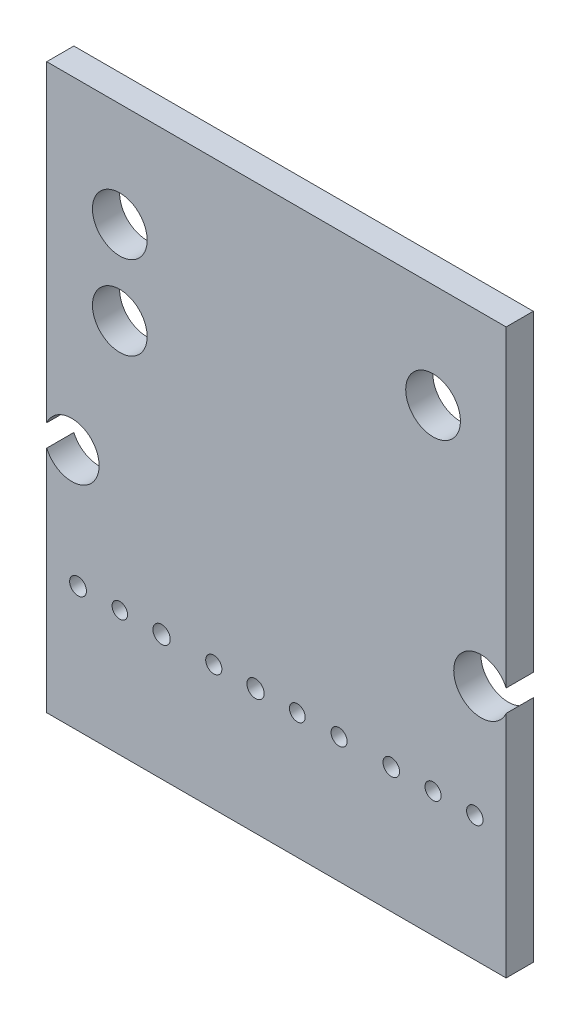
SolidWorks part; units mm, degrees
ref_plane "Front" through (0, 0, 0) normal (0, 0, 1) x (1, 0, 0)
ref_plane "Top" through (0, 0, 0) normal (0, 1, 0) x (1, 0, 0)
ref_plane "Right" through (0, 0, 0) normal (1, 0, 0) x (0, 0, -1)
sketch "Model" plane through (0, 0, 0) normal (0, 0, 1) x (1, 0, 0)
  line L0 (0.0762, 0) -> (0.0762, 34.29)
  line L1 (-0.0762, 34.29) -> (-0.0762, 0)
  line L2 (0, 34.2138) -> (27.94, 34.2138)
  line L3 (27.94, 34.3662) -> (0, 34.3662)
  line L4 (27.8638, 34.29) -> (27.8638, 0)
  line L5 (28.0162, 0) -> (28.0162, 34.29)
  line L6 (27.94, 0.0762) -> (0, 0.0762)
  line L7 (0, -0.0762) -> (27.94, -0.0762)
  line L8 (15.1638, 21.336) -> (15.1638, 19.1135)
  line L9 (15.3162, 19.1135) -> (15.3162, 21.336)
  line L10 (15.24, 19.0373) -> (18.6055, 19.0373)
  line L11 (18.6055, 19.1897) -> (15.24, 19.1897)
  line L12 (18.6817, 19.1135) -> (18.6817, 21.3995)
  line L13 (18.5293, 21.3995) -> (18.5293, 19.1135)
  line L14 (18.6055, 21.4757) -> (15.24, 21.4757)
  line L15 (15.24, 21.3233) -> (18.6055, 21.3233)
  line L16 (1.9255, 9.8453) -> (1.4521, 10.1036)
  line L17 (1.3913, 9.9921) -> (1.8647, 9.7338)
  line L18 (20.9755, 9.7183) -> (20.5021, 9.9766)
  line L19 (20.4413, 9.8651) -> (20.9147, 9.6068)
  line L20 (3.8735, 9.0805) -> (4.39, 9.0805)
  line L21 (4.39, 9.2075) -> (3.8735, 9.2075)
  line L22 (4.7978, 9.4883) -> (4.7978, 9.6605)
  line L23 (4.6708, 9.6605) -> (4.6708, 9.4883)
  line L24 (4.39, 10.0683) -> (3.8735, 10.0683)
  line L25 (3.8735, 9.9413) -> (4.39, 9.9413)
  line L26 (3.937, 10.0048) -> (3.937, 10.6934)
  line L27 (3.81, 10.6934) -> (3.81, 10.0048)
  line L28 (3.8735, 10.6299) -> (4.7343, 10.6299)
  line L29 (4.7343, 10.7569) -> (3.8735, 10.7569)
  line L30 (22.987, 8.9535) -> (23.5035, 8.9535)
  line L31 (23.5035, 9.0805) -> (22.987, 9.0805)
  line L32 (23.9113, 9.3613) -> (23.9113, 9.5335)
  line L33 (23.7843, 9.5335) -> (23.7843, 9.3613)
  line L34 (23.5035, 9.9413) -> (22.987, 9.9413)
  line L35 (22.987, 9.8143) -> (23.5035, 9.8143)
  line L36 (23.0505, 9.8778) -> (23.0505, 10.5664)
  line L37 (22.9235, 10.5664) -> (22.9235, 9.8778)
  line L38 (22.987, 10.5029) -> (23.8478, 10.5029)
  line L39 (23.8478, 10.6299) -> (22.987, 10.6299)
  line L40 (6.635, 9.9413) -> (6.8933, 9.9413)
  line L41 (6.8933, 10.0683) -> (6.635, 10.0683)
  line L42 (6.8298, 10.0048) -> (6.8298, 9.144)
  line L43 (6.9568, 9.144) -> (6.9568, 10.0048)
  line L44 (6.8933, 9.2075) -> (6.3768, 9.2075)
  line L45 (6.3768, 9.0805) -> (6.8933, 9.0805)
  line L46 (6.096, 9.4883) -> (6.096, 10.3491)
  line L47 (5.969, 10.3491) -> (5.969, 9.4883)
  line L48 (6.3768, 10.6299) -> (6.8933, 10.6299)
  line L49 (6.8933, 10.7569) -> (6.3768, 10.7569)
  line L50 (17.4935, 9.7508) -> (17.7518, 9.7508)
  line L51 (17.7518, 9.8778) -> (17.4935, 9.8778)
  line L52 (17.6883, 9.8143) -> (17.6883, 8.9535)
  line L53 (17.8153, 8.9535) -> (17.8153, 9.8143)
  line L54 (17.7518, 9.017) -> (17.2353, 9.017)
  line L55 (17.2353, 8.89) -> (17.7518, 8.89)
  line L56 (16.9545, 9.2978) -> (16.9545, 10.1586)
  line L57 (16.8275, 10.1586) -> (16.8275, 9.2978)
  line L58 (17.2353, 10.4394) -> (17.7518, 10.4394)
  line L59 (17.7518, 10.5664) -> (17.2353, 10.5664)
  line L60 (25.7485, 9.8143) -> (26.0068, 9.8143)
  line L61 (26.0068, 9.9413) -> (25.7485, 9.9413)
  line L62 (25.9433, 9.8778) -> (25.9433, 9.017)
  line L63 (26.0703, 9.017) -> (26.0703, 9.8778)
  line L64 (26.0068, 9.0805) -> (25.4903, 9.0805)
  line L65 (25.4903, 8.9535) -> (26.0068, 8.9535)
  line L66 (25.2095, 9.3613) -> (25.2095, 10.2221)
  line L67 (25.0825, 10.2221) -> (25.0825, 9.3613)
  line L68 (25.4903, 10.5029) -> (26.0068, 10.5029)
  line L69 (26.0068, 10.6299) -> (25.4903, 10.6299)
  line L70 (8.413, 14.0053) -> (8.6713, 14.0053)
  line L71 (8.6713, 14.1323) -> (8.413, 14.1323)
  line L72 (8.6078, 14.0688) -> (8.6078, 13.208)
  line L73 (8.7348, 13.208) -> (8.7348, 14.0688)
  line L74 (8.6713, 13.2715) -> (8.1548, 13.2715)
  line L75 (8.1548, 13.1445) -> (8.6713, 13.1445)
  line L76 (7.874, 13.5523) -> (7.874, 14.4131)
  line L77 (7.747, 14.4131) -> (7.747, 13.5523)
  line L78 (8.1548, 14.6939) -> (8.6713, 14.6939)
  line L79 (8.6713, 14.8209) -> (8.1548, 14.8209)
  line L80 (6.5405, 15.6845) -> (6.9709, 15.6845)
  line L81 (6.9709, 15.8115) -> (6.5405, 15.8115)
  line L82 (6.5405, 17.2339) -> (7.057, 17.2339)
  line L83 (7.057, 17.3609) -> (6.5405, 17.3609)
  line L84 (7.057, 16.6723) -> (6.7127, 16.6723)
  line L85 (6.7127, 16.5453) -> (7.057, 16.5453)
  line L86 (8.032, 15.748) -> (8.032, 15.8341)
  line L87 (7.905, 15.8341) -> (7.905, 15.748)
  line L88 (7.9685, 15.7706) -> (8.0545, 15.7706)
  line L89 (8.0545, 15.8976) -> (7.9685, 15.8976)
  line L90 (7.991, 15.8341) -> (7.991, 15.748)
  line L91 (8.118, 15.748) -> (8.118, 15.8341)
  line L92 (8.0545, 15.8115) -> (7.9685, 15.8115)
  line L93 (7.9685, 15.6845) -> (8.0545, 15.6845)
  line L94 (8.6217, 15.6845) -> (9.0521, 15.6845)
  line L95 (9.0521, 15.8115) -> (8.6217, 15.8115)
  line L96 (8.6217, 17.2339) -> (9.1382, 17.2339)
  line L97 (9.1382, 17.3609) -> (8.6217, 17.3609)
  line L98 (9.1382, 16.6723) -> (8.7939, 16.6723)
  line L99 (8.7939, 16.5453) -> (9.1382, 16.5453)
  line L100 (14.5382, 8.8064) -> (15.0547, 10.3558)
  line L101 (14.9342, 10.396) -> (14.4178, 8.8466)
  line L102 (14.9342, 10.3558) -> (15.4507, 8.8064)
  line L103 (15.5712, 8.8466) -> (15.0547, 10.396)
  line L104 (15.3818, 9.2774) -> (14.6071, 9.2774)
  line L105 (14.6071, 9.1503) -> (15.3818, 9.1503)
  line L106 (9.5885, 9.7508) -> (10.0189, 9.7508)
  line L107 (10.0189, 9.8778) -> (9.5885, 9.8778)
  line L108 (10.0189, 9.017) -> (9.5885, 9.017)
  line L109 (9.5885, 8.89) -> (10.0189, 8.89)
  line L110 (9.652, 8.9535) -> (9.652, 10.5029)
  line L111 (9.525, 10.5029) -> (9.525, 8.9535)
  line L112 (9.5885, 10.4394) -> (10.0189, 10.4394)
  line L113 (10.0189, 10.5664) -> (9.5885, 10.5664)
  line L114 (12.065, 9.429) -> (13.0979, 9.429)
  line L115 (13.0979, 9.556) -> (12.065, 9.556)
  line L116 (12.645, 8.9761) -> (12.645, 10.009)
  line L117 (12.518, 10.009) -> (12.518, 8.9761)
  line L118 (6.6642, 18.4584) -> (7.1807, 20.0078)
  line L119 (7.0602, 20.048) -> (6.5438, 18.4986)
  line L120 (7.0602, 20.0078) -> (7.5767, 18.4584)
  line L121 (7.6972, 18.4986) -> (7.1807, 20.048)
  line L122 (7.5078, 18.9293) -> (6.7331, 18.9293)
  line L123 (6.7331, 18.8024) -> (7.5078, 18.8024)
  line L124 (8.2767, 18.4785) -> (8.2767, 19.5114)
  line L125 (8.1497, 19.5114) -> (8.1497, 18.4785)
  line L126 (8.2132, 19.4479) -> (8.6436, 19.4479)
  line L127 (8.6436, 19.5749) -> (8.2132, 19.5749)
  line L128 (8.8383, 19.2532) -> (8.8383, 18.4785)
  line L129 (8.9653, 18.4785) -> (8.9653, 19.2532)
  line L130 (18.6507, 23.9649) -> (18.6507, 22.4155)
  line L131 (18.7777, 22.4155) -> (18.7777, 23.9649)
  line L132 (18.542, 22.352) -> (18.8863, 22.352)
  line L133 (18.8863, 22.479) -> (18.542, 22.479)
  line L134 (18.542, 23.9014) -> (18.8863, 23.9014)
  line L135 (18.8863, 24.0284) -> (18.542, 24.0284)
  line L136 (19.5731, 22.4155) -> (19.5731, 23.4484)
  line L137 (19.4461, 23.4484) -> (19.4461, 22.4155)
  line L138 (19.5096, 23.3849) -> (19.9399, 23.3849)
  line L139 (19.9399, 23.5119) -> (19.5096, 23.5119)
  line L140 (20.1347, 23.1902) -> (20.1347, 22.4155)
  line L141 (20.2617, 22.4155) -> (20.2617, 23.1902)
  line L142 (21.4657, 23.9649) -> (21.4657, 22.4155)
  line L143 (21.5927, 22.4155) -> (21.5927, 23.9649)
  line L144 (21.5292, 22.479) -> (21.0989, 22.479)
  line L145 (21.0989, 22.352) -> (21.5292, 22.352)
  line L146 (20.9041, 22.6737) -> (20.9041, 23.1902)
  line L147 (20.7771, 23.1902) -> (20.7771, 22.6737)
  line L148 (21.0989, 23.3849) -> (21.5292, 23.3849)
  line L149 (21.5292, 23.5119) -> (21.0989, 23.5119)
  line L150 (22.1887, 22.3803) -> (22.8773, 23.4132)
  line L151 (22.7716, 23.4836) -> (22.083, 22.4507)
  line L152 (22.083, 23.4132) -> (22.7716, 22.3803)
  line L153 (22.8773, 22.4507) -> (22.1887, 23.4836)
  line L154 (13.6525, 19.177) -> (14.169, 19.177)
  line L155 (14.169, 19.304) -> (13.6525, 19.304)
  line L156 (14.5768, 19.5848) -> (14.5768, 19.757)
  line L157 (14.4498, 19.757) -> (14.4498, 19.5848)
  line L158 (14.169, 20.1648) -> (13.6525, 20.1648)
  line L159 (13.6525, 20.0378) -> (14.169, 20.0378)
  line L160 (13.716, 20.1013) -> (13.716, 20.7899)
  line L161 (13.589, 20.7899) -> (13.589, 20.1013)
  line L162 (13.6525, 20.7264) -> (14.5133, 20.7264)
  line L163 (14.5133, 20.8534) -> (13.6525, 20.8534)
  line L164 (18.9865, 19.177) -> (19.4169, 19.177)
  line L165 (19.4169, 19.304) -> (18.9865, 19.304)
  line L166 (18.9865, 20.7264) -> (19.503, 20.7264)
  line L167 (19.503, 20.8534) -> (18.9865, 20.8534)
  line L168 (19.503, 20.1648) -> (19.1587, 20.1648)
  line L169 (19.1587, 20.0378) -> (19.503, 20.0378)
  line L170 (20.478, 19.2405) -> (20.478, 19.3266)
  line L171 (20.351, 19.3266) -> (20.351, 19.2405)
  line L172 (20.4145, 19.2631) -> (20.5005, 19.2631)
  line L173 (20.5005, 19.3901) -> (20.4145, 19.3901)
  line L174 (20.437, 19.3266) -> (20.437, 19.2405)
  line L175 (20.564, 19.2405) -> (20.564, 19.3266)
  line L176 (20.5005, 19.304) -> (20.4145, 19.304)
  line L177 (20.4145, 19.177) -> (20.5005, 19.177)
  line L178 (21.0677, 19.177) -> (21.4981, 19.177)
  line L179 (21.4981, 19.304) -> (21.0677, 19.304)
  line L180 (21.0677, 20.7264) -> (21.5842, 20.7264)
  line L181 (21.5842, 20.8534) -> (21.0677, 20.8534)
  line L182 (21.5842, 20.1648) -> (21.2399, 20.1648)
  line L183 (21.2399, 20.0378) -> (21.5842, 20.0378)
  line L184 (20.8915, 2.794) -> (20.8915, 4.3434)
  line L185 (20.7645, 4.3434) -> (20.7645, 2.794)
  line L186 (20.828, 4.2799) -> (21.5166, 4.2799)
  line L187 (21.5166, 4.4069) -> (20.828, 4.4069)
  line L188 (20.828, 3.5913) -> (21.5166, 3.5913)
  line L189 (21.5166, 3.7183) -> (20.828, 3.7183)
  line L190 (21.9421, 4.3296) -> (22.2864, 2.7802)
  line L191 (22.4104, 2.8078) -> (22.066, 4.3572)
  line L192 (22.4086, 2.7739) -> (22.7529, 3.8069)
  line L193 (22.6324, 3.847) -> (22.2881, 2.8141)
  line L194 (22.6324, 3.8069) -> (22.9768, 2.7739)
  line L195 (23.0972, 2.8141) -> (22.7529, 3.847)
  line L196 (23.099, 2.7802) -> (23.4433, 4.3296)
  line L197 (23.3193, 4.3572) -> (22.975, 2.8078)
  line L198 (24.0602, 2.794) -> (24.0602, 4.3434)
  line L199 (23.9332, 4.3434) -> (23.9332, 2.794)
  line L200 (23.9966, 4.2799) -> (24.427, 4.2799)
  line L201 (24.427, 4.4069) -> (23.9966, 4.4069)
  line L202 (24.7939, 3.913) -> (24.7939, 3.2244)
  line L203 (24.9209, 3.2244) -> (24.9209, 3.913)
  line L204 (24.427, 2.8575) -> (23.9966, 2.8575)
  line L205 (23.9966, 2.7305) -> (24.427, 2.7305)
  line L206 (2.2225, 2.921) -> (2.2225, 4.4704)
  line L207 (2.0955, 4.4704) -> (2.0955, 2.921)
  line L208 (2.159, 4.4069) -> (2.5894, 4.4069)
  line L209 (2.5894, 4.5339) -> (2.159, 4.5339)
  line L210 (2.5894, 3.6731) -> (2.159, 3.6731)
  line L211 (2.159, 3.5461) -> (2.5894, 3.5461)
  line L212 (3.0766, 2.9494) -> (2.7323, 3.638)
  line L213 (2.6187, 3.5812) -> (2.963, 2.8926)
  line L214 (4.3779, 2.9845) -> (3.6893, 2.9845)
  line L215 (3.6893, 2.8575) -> (4.3779, 2.8575)
  line L216 (3.7528, 2.921) -> (3.7528, 4.4704)
  line L217 (3.6258, 4.4704) -> (3.6258, 2.921)
  line L218 (3.6893, 4.4069) -> (4.3779, 4.4069)
  line L219 (4.3779, 4.5339) -> (3.6893, 4.5339)
  line L220 (3.6893, 3.7183) -> (4.2058, 3.7183)
  line L221 (4.2058, 3.8453) -> (3.6893, 3.8453)
  line L222 (4.7791, 4.4503) -> (5.2955, 2.9009)
  line L223 (5.416, 2.9411) -> (4.8996, 4.4905)
  line L224 (5.416, 2.9009) -> (5.9325, 4.4503)
  line L225 (5.812, 4.4905) -> (5.2955, 2.9411)
  line L226 (10.8486, 2.9845) -> (10.16, 2.9845)
  line L227 (10.16, 2.8575) -> (10.8486, 2.8575)
  line L228 (10.2235, 2.921) -> (10.2235, 4.4704)
  line L229 (10.0965, 4.4704) -> (10.0965, 2.921)
  line L230 (10.16, 4.4069) -> (10.8486, 4.4069)
  line L231 (10.8486, 4.5339) -> (10.16, 4.5339)
  line L232 (10.16, 3.7183) -> (10.6765, 3.7183)
  line L233 (10.6765, 3.8453) -> (10.16, 3.8453)
  line L234 (11.4961, 2.921) -> (11.4961, 3.9539)
  line L235 (11.3691, 3.9539) -> (11.3691, 2.921)
  line L236 (11.4326, 3.8904) -> (11.863, 3.8904)
  line L237 (11.863, 4.0174) -> (11.4326, 4.0174)
  line L238 (12.0577, 3.6957) -> (12.0577, 2.921)
  line L239 (12.1847, 2.921) -> (12.1847, 3.6957)
  line L240 (13.3747, 2.9845) -> (13.0304, 2.9845)
  line L241 (13.0304, 2.8575) -> (13.3747, 2.8575)
  line L242 (12.8356, 3.1792) -> (12.8356, 3.6957)
  line L243 (12.7086, 3.6957) -> (12.7086, 3.1792)
  line L244 (13.0304, 3.8904) -> (13.3747, 3.8904)
  line L245 (13.3747, 4.0174) -> (13.0304, 4.0174)
  line L246 (13.9737, 3.2653) -> (13.9737, 3.6096)
  line L247 (13.8467, 3.6096) -> (13.8467, 3.2653)
  line L248 (14.5354, 3.6096) -> (14.5354, 3.2653)
  line L249 (14.6624, 3.2653) -> (14.6624, 3.6096)
  line L250 (15.8169, 4.4704) -> (15.8169, 2.921)
  line L251 (15.9439, 2.921) -> (15.9439, 4.4704)
  line L252 (15.8804, 2.9845) -> (15.45, 2.9845)
  line L253 (15.45, 2.8575) -> (15.8804, 2.8575)
  line L254 (15.2553, 3.1792) -> (15.2553, 3.6957)
  line L255 (15.1283, 3.6957) -> (15.1283, 3.1792)
  line L256 (15.45, 3.8904) -> (15.8804, 3.8904)
  line L257 (15.8804, 4.0174) -> (15.45, 4.0174)
  line L258 (17.2252, 2.9845) -> (16.7948, 2.9845)
  line L259 (16.7948, 2.8575) -> (17.2252, 2.8575)
  line L260 (16.6, 3.1792) -> (16.6, 3.6096)
  line L261 (16.473, 3.6096) -> (16.473, 3.1792)
  line L262 (17.1617, 3.6096) -> (17.1617, 3.4375)
  line L263 (17.2887, 3.4375) -> (17.2887, 3.6096)
  line L264 (17.2252, 3.501) -> (16.5365, 3.501)
  line L265 (16.5365, 3.374) -> (17.2252, 3.374)
  line L266 (17.9458, 2.921) -> (17.9458, 3.9539)
  line L267 (17.8188, 3.9539) -> (17.8188, 2.921)
  line L268 (17.8823, 3.8904) -> (18.3988, 3.8904)
  line L269 (18.3988, 4.0174) -> (17.8823, 4.0174)
  line L270 (18.3353, 3.9539) -> (18.3353, 3.7818)
  line L271 (18.4623, 3.7818) -> (18.4623, 3.9539)
  line L272 (6.1454, 30.9245) -> (6.1454, 32.4739)
  line L273 (6.0184, 32.4739) -> (6.0184, 30.9245)
  line L274 (5.6515, 32.4104) -> (6.5123, 32.4104)
  line L275 (6.5123, 32.5374) -> (5.6515, 32.5374)
  line L276 (7.0131, 30.9044) -> (7.5296, 32.4538)
  line L277 (7.4091, 32.494) -> (6.8926, 30.9446)
  line L278 (7.4091, 32.4538) -> (7.9256, 30.9044)
  line L279 (8.0461, 30.9446) -> (7.5296, 32.494)
  line L280 (7.8567, 31.3753) -> (7.082, 31.3753)
  line L281 (7.082, 31.2484) -> (7.8567, 31.2484)
  line L282 (8.5143, 32.4739) -> (8.5143, 30.9245)
  line L283 (8.6413, 30.9245) -> (8.6413, 32.4739)
  line L284 (8.5778, 30.861) -> (9.2665, 30.861)
  line L285 (9.2665, 30.988) -> (8.5778, 30.988)
  line L286 (9.8774, 31.3549) -> (9.8774, 32.0435)
  line L287 (9.7504, 32.0435) -> (9.7504, 31.3549)
  line L288 (10.6112, 32.0435) -> (10.6112, 31.3549)
  line L289 (10.7382, 31.3549) -> (10.7382, 32.0435)
  line L290 (11.4135, 30.9245) -> (11.4135, 32.4739)
  line L291 (11.2865, 32.4739) -> (11.2865, 30.9245)
  line L292 (11.2945, 32.4431) -> (12.1553, 30.8937)
  line L293 (12.2663, 30.9553) -> (11.4056, 32.5047)
  line L294 (12.2743, 30.9245) -> (12.2743, 32.4739)
  line L295 (12.1473, 32.4739) -> (12.1473, 30.9245)
  line L296 (13.7483, 31.7218) -> (14.1787, 31.7218)
  line L297 (14.1787, 31.8488) -> (13.7483, 31.8488)
  line L298 (14.1787, 30.988) -> (13.7483, 30.988)
  line L299 (13.7483, 30.861) -> (14.1787, 30.861)
  line L300 (13.8118, 30.9245) -> (13.8118, 32.4739)
  line L301 (13.6848, 32.4739) -> (13.6848, 30.9245)
  line L302 (13.7483, 32.4104) -> (14.1787, 32.4104)
  line L303 (14.1787, 32.5374) -> (13.7483, 32.5374)
  line L304 (15.2735, 30.9245) -> (15.2735, 31.9574)
  line L305 (15.1465, 31.9574) -> (15.1465, 30.9245)
  line L306 (15.21, 31.8939) -> (15.7264, 31.8939)
  line L307 (15.7264, 32.0209) -> (15.21, 32.0209)
  line L308 (15.6629, 31.9574) -> (15.6629, 31.7853)
  line L309 (15.7899, 31.7853) -> (15.7899, 31.9574)
  line L310 (16.8818, 30.988) -> (16.4514, 30.988)
  line L311 (16.4514, 30.861) -> (16.8818, 30.861)
  line L312 (16.2567, 31.1827) -> (16.2567, 31.6131)
  line L313 (16.1297, 31.6131) -> (16.1297, 31.1827)
  line L314 (16.8183, 31.6131) -> (16.8183, 31.441)
  line L315 (16.9453, 31.441) -> (16.9453, 31.6131)
  line L316 (16.8818, 31.5045) -> (16.1932, 31.5045)
  line L317 (16.1932, 31.3775) -> (16.8818, 31.3775)
  line L318 (18.1633, 31.5905) -> (17.776, 31.5905)
  line L319 (17.776, 31.4635) -> (18.1633, 31.4635)
  line L320 (17.776, 30.861) -> (18.1633, 30.861)
  line L321 (18.1633, 30.988) -> (17.776, 30.988)
  line L322 (18.2268, 30.9245) -> (18.2268, 31.6992)
  line L323 (18.0998, 31.6992) -> (18.0998, 30.9245)
  line L324 (17.9051, 32.0209) -> (17.5608, 32.0209)
  line L325 (17.5608, 31.8939) -> (17.9051, 31.8939)
  line L326 (18.9483, 30.9245) -> (18.9483, 32.4739)
  line L327 (18.8213, 32.4739) -> (18.8213, 30.9245)
  line L328 (19.5353, 32.0082) -> (18.8467, 31.4918)
  line L329 (18.9229, 31.3902) -> (19.6115, 31.9066)
  line L330 (19.6295, 30.9542) -> (19.2422, 31.6859)
  line L331 (19.1299, 31.6265) -> (19.5173, 30.8948)
  line L332 (20.1713, 31.2688) -> (20.1713, 31.6131)
  line L333 (20.0443, 31.6131) -> (20.0443, 31.2688)
  line L334 (20.733, 31.6131) -> (20.733, 31.2688)
  line L335 (20.86, 31.2688) -> (20.86, 31.6131)
  line L336 (21.3823, 31.9574) -> (21.3823, 31.1827)
  line L337 (21.5093, 31.1827) -> (21.5093, 31.9574)
  line L338 (21.704, 30.861) -> (22.1344, 30.861)
  line L339 (22.1344, 30.988) -> (21.704, 30.988)
  line L340 (22.1979, 30.9245) -> (22.1979, 31.9574)
  line L341 (22.0709, 31.9574) -> (22.0709, 30.9245)
  line L342 (22.6607, 31.8939) -> (23.1772, 31.8939)
  line L343 (23.1772, 32.0209) -> (22.6607, 32.0209)
  line L344 (22.7694, 32.4739) -> (22.7694, 31.1827)
  line L345 (22.8964, 31.1827) -> (22.8964, 32.4739)
  line L346 (23.0911, 30.861) -> (23.1772, 30.861)
  line L347 (23.1772, 30.988) -> (23.0911, 30.988)
  line L348 (7.9911, 28.194) -> (7.3025, 28.194)
  line L349 (7.3025, 28.067) -> (7.9911, 28.067)
  line L350 (7.366, 28.1305) -> (7.366, 29.6799)
  line L351 (7.239, 29.6799) -> (7.239, 28.1305)
  line L352 (7.3025, 29.6164) -> (7.9911, 29.6164)
  line L353 (7.9911, 29.7434) -> (7.3025, 29.7434)
  line L354 (7.3025, 28.9278) -> (7.819, 28.9278)
  line L355 (7.819, 29.0548) -> (7.3025, 29.0548)
  line L356 (8.6713, 28.1305) -> (8.6713, 29.6799)
  line L357 (8.5443, 29.6799) -> (8.5443, 28.1305)
  line L358 (8.6078, 29.6164) -> (9.0382, 29.6164)
  line L359 (9.0382, 29.7434) -> (8.6078, 29.7434)
  line L360 (9.0382, 28.8826) -> (8.6078, 28.8826)
  line L361 (8.6078, 28.7556) -> (9.0382, 28.7556)
  line L362 (10.0947, 29.6799) -> (10.0947, 28.1305)
  line L363 (10.2217, 28.1305) -> (10.2217, 29.6799)
  line L364 (9.9861, 28.067) -> (10.3304, 28.067)
  line L365 (10.3304, 28.194) -> (9.9861, 28.194)
  line L366 (9.9861, 29.6164) -> (10.3304, 29.6164)
  line L367 (10.3304, 29.7434) -> (9.9861, 29.7434)
  line L368 (11.602, 28.194) -> (11.2577, 28.194)
  line L369 (11.2577, 28.067) -> (11.602, 28.067)
  line L370 (10.9769, 28.4748) -> (10.9769, 29.3356)
  line L371 (10.8499, 29.3356) -> (10.8499, 28.4748)
  line L372 (11.2577, 29.6164) -> (11.602, 29.6164)
  line L373 (11.602, 29.7434) -> (11.2577, 29.7434)
  line L374 (13.0704, 28.1305) -> (13.0704, 29.6799)
  line L375 (12.9434, 29.6799) -> (12.9434, 28.1305)
  line L376 (13.0069, 29.6164) -> (13.4373, 29.6164)
  line L377 (13.4373, 29.7434) -> (13.0069, 29.7434)
  line L378 (13.4373, 28.8826) -> (13.0069, 28.8826)
  line L379 (13.0069, 28.7556) -> (13.4373, 28.7556)
  line L380 (13.9245, 28.1589) -> (13.5801, 28.8475)
  line L381 (13.4665, 28.7907) -> (13.8109, 28.1021)
  line L382 (14.5354, 28.4748) -> (14.5354, 28.8191)
  line L383 (14.4084, 28.8191) -> (14.4084, 28.4748)
  line L384 (15.097, 28.8191) -> (15.097, 28.4748)
  line L385 (15.224, 28.4748) -> (15.224, 28.8191)
  line L386 (15.7531, 29.6799) -> (15.7531, 28.1305)
  line L387 (15.8801, 28.1305) -> (15.8801, 29.6799)
  line L388 (15.8166, 28.067) -> (16.247, 28.067)
  line L389 (16.247, 28.194) -> (15.8166, 28.194)
  line L390 (16.5688, 28.3887) -> (16.5688, 28.9052)
  line L391 (16.4418, 28.9052) -> (16.4418, 28.3887)
  line L392 (16.247, 29.2269) -> (15.8166, 29.2269)
  line L393 (15.8166, 29.0999) -> (16.247, 29.0999)
  line L394 (17.1617, 28.4748) -> (17.1617, 28.8191)
  line L395 (17.0347, 28.8191) -> (17.0347, 28.4748)
  line L396 (17.7233, 28.8191) -> (17.7233, 28.4748)
  line L397 (17.8503, 28.4748) -> (17.8503, 28.8191)
  line L398 (18.2636, 29.0999) -> (18.78, 29.0999)
  line L399 (18.78, 29.2269) -> (18.2636, 29.2269)
  line L400 (18.3723, 29.6799) -> (18.3723, 28.3887)
  line L401 (18.4993, 28.3887) -> (18.4993, 29.6799)
  line L402 (18.694, 28.067) -> (18.78, 28.067)
  line L403 (18.78, 28.194) -> (18.694, 28.194)
  line L404 (19.2785, 29.0999) -> (19.9671, 29.0999)
  line L405 (19.9671, 29.2269) -> (19.2785, 29.2269)
  line L406 (19.9143, 29.1986) -> (19.2256, 28.1657)
  line L407 (19.3313, 28.0953) -> (20.0199, 29.1282)
  line L408 (19.2785, 28.067) -> (19.9671, 28.067)
  line L409 (19.9671, 28.194) -> (19.2785, 28.194)
  line L410 (7.493, 25.2095) -> (7.493, 26.7589)
  line L411 (7.366, 26.7589) -> (7.366, 25.2095)
  line L412 (7.4295, 26.6954) -> (8.1181, 26.6954)
  line L413 (8.1181, 26.8224) -> (7.4295, 26.8224)
  line L414 (7.4295, 26.0068) -> (8.1181, 26.0068)
  line L415 (8.1181, 26.1338) -> (7.4295, 26.1338)
  line L416 (9.3343, 25.8755) -> (8.947, 25.8755)
  line L417 (8.947, 25.7485) -> (9.3343, 25.7485)
  line L418 (8.947, 25.146) -> (9.3343, 25.146)
  line L419 (9.3343, 25.273) -> (8.947, 25.273)
  line L420 (9.3978, 25.2095) -> (9.3978, 25.9842)
  line L421 (9.2708, 25.9842) -> (9.2708, 25.2095)
  line L422 (9.0761, 26.3059) -> (8.7318, 26.3059)
  line L423 (8.7318, 26.1789) -> (9.0761, 26.1789)
  line L424 (9.9499, 26.7589) -> (9.9499, 25.4677)
  line L425 (10.0769, 25.4677) -> (10.0769, 26.7589)
  line L426 (10.7427, 26.7589) -> (10.7427, 25.4677)
  line L427 (10.8697, 25.4677) -> (10.8697, 26.7589)
  line L428 (13.0653, 26.1114) -> (12.3337, 25.2506)
  line L429 (12.4304, 25.1684) -> (13.1621, 26.0292)
  line L430 (12.382, 25.146) -> (13.2428, 25.146)
  line L431 (13.2428, 25.273) -> (12.382, 25.273)
  line L432 (14.0043, 25.5141) -> (14.6929, 26.3749)
  line L433 (14.5937, 26.4543) -> (13.9051, 25.5935)
  line L434 (15.3949, 26.365) -> (15.8252, 26.7093)
  line L435 (15.7459, 26.8085) -> (15.3155, 26.4642)
  line L436 (15.7221, 26.7589) -> (15.7221, 25.2095)
  line L437 (15.8491, 25.2095) -> (15.8491, 26.7589)
  line L438 (15.3552, 25.146) -> (16.216, 25.146)
  line L439 (16.216, 25.273) -> (15.3552, 25.273)
  line L440 (19.1342, 25.7485) -> (20.1671, 25.7485)
  line L441 (20.1671, 25.8755) -> (19.1342, 25.8755)
  line L442 (21.476, 26.2224) -> (21.8203, 25.1894)
  line L443 (21.9408, 25.2296) -> (21.5965, 26.2625)
  line L444 (21.9408, 25.1894) -> (22.2851, 26.2224)
  line L445 (22.1646, 26.2625) -> (21.8203, 25.2296)
  line L446 (23.4714, 26.1114) -> (22.7397, 25.2506)
  line L447 (22.8365, 25.1684) -> (23.5681, 26.0292)
  line L448 (22.7881, 25.146) -> (23.6488, 25.146)
  line L449 (23.6488, 25.273) -> (22.7881, 25.273)
  line L450 (15.9639, 20.32) -> (16.002, 20.32)
  circle A0 centre (17.018, 23.114) radius 0.8382
  circle A1 centre (17.018, 23.114) radius 0.8382
  circle A2 centre (11.049, 19.05) radius 0.8382
  circle A3 centre (11.049, 19.05) radius 0.8382
  circle A4 centre (11.049, 16.51) radius 0.8382
  circle A5 centre (11.049, 16.51) radius 0.8382
  circle A6 centre (11.049, 13.97) radius 0.8382
  circle A7 centre (11.049, 13.97) radius 0.8382
  circle A8 centre (20.955, 7.62) radius 0.8382
  circle A9 centre (20.955, 7.62) radius 0.8382
  circle A10 centre (23.495, 7.62) radius 0.8382
  circle A11 centre (23.495, 7.62) radius 0.8382
  circle A12 centre (26.035, 7.62) radius 0.8382
  circle A13 centre (26.035, 7.62) radius 0.8382
  circle A14 centre (1.905, 7.62) radius 0.8382
  circle A15 centre (1.905, 7.62) radius 0.8382
  circle A16 centre (4.445, 7.62) radius 0.8382
  circle A17 centre (4.445, 7.62) radius 0.8382
  circle A18 centre (6.985, 7.62) radius 0.8382
  circle A19 centre (6.985, 7.62) radius 0.8382
  circle A20 centre (10.16, 7.62) radius 0.8382
  circle A21 centre (10.16, 7.62) radius 0.8382
  circle A22 centre (12.7, 7.62) radius 0.8382
  circle A23 centre (12.7, 7.62) radius 0.8382
  circle A24 centre (15.24, 7.62) radius 0.8382
  circle A25 centre (15.24, 7.62) radius 0.8382
  circle A26 centre (17.78, 7.62) radius 0.8382
  circle A27 centre (17.78, 7.62) radius 0.8382
  circle A28 centre (11.049, 22.86) radius 0.4032
  circle A29 centre (11.049, 22.86) radius 0.4032
  circle A30 centre (11.049, 21.082) radius 0.4032
  circle A31 centre (11.049, 21.082) radius 0.4032
  circle A32 centre (4.445, 12.7) radius 0.4032
  circle A33 centre (4.445, 12.7) radius 0.4032
  circle A34 centre (23.495, 16.51) radius 0.4032
  circle A35 centre (23.495, 16.51) radius 0.4032
  circle A36 centre (23.495, 21.59) radius 0.4032
  circle A37 centre (23.495, 21.59) radius 0.4032
  circle A38 centre (17.145, 16.5735) radius 0.4032
  circle A39 centre (17.145, 16.5735) radius 0.4032
  circle A40 centre (17.145, 13.97) radius 0.4032
  circle A41 centre (17.145, 13.97) radius 0.4032
  circle A42 centre (4.445, 17.78) radius 0.4032
  circle A43 centre (4.445, 17.78) radius 0.4032
  circle A44 centre (4.445, 15.24) radius 0.4032
  circle A45 centre (4.445, 15.24) radius 0.4032
  circle A46 centre (4.445, 27.94) radius 1.5113
  circle A47 centre (4.445, 27.94) radius 1.6637
  circle A48 centre (23.495, 27.94) radius 1.5113
  circle A49 centre (23.495, 27.94) radius 1.6637
  circle A50 centre (1.524, 14.605) radius 1.5113
  circle A51 centre (1.524, 14.605) radius 1.6637
  circle A52 centre (26.416, 14.605) radius 1.5113
  circle A53 centre (26.416, 14.605) radius 1.6637
  circle A54 centre (4.445, 22.86) radius 1.5113
  circle A55 centre (4.445, 22.86) radius 1.6637
  circle A56 centre (17.018, 23.114) radius 0.5
  circle A57 centre (11.049, 19.05) radius 0.5
  circle A58 centre (11.049, 16.51) radius 0.5
  circle A59 centre (11.049, 13.97) radius 0.5
  circle A60 centre (20.955, 7.62) radius 0.5
  circle A61 centre (23.495, 7.62) radius 0.5
  circle A62 centre (26.035, 7.62) radius 0.5
  circle A63 centre (1.905, 7.62) radius 0.5
  circle A64 centre (4.445, 7.62) radius 0.5
  circle A65 centre (6.985, 7.62) radius 0.5
  circle A66 centre (10.16, 7.62) radius 0.5
  circle A67 centre (12.7, 7.62) radius 0.5
  circle A68 centre (15.24, 7.62) radius 0.5
  circle A69 centre (17.78, 7.62) radius 0.5
  circle A70 centre (11.049, 22.86) radius 0.2
  circle A71 centre (11.049, 21.082) radius 0.2
  circle A72 centre (4.445, 12.7) radius 0.2
  circle A73 centre (23.495, 16.51) radius 0.2
  circle A74 centre (23.495, 21.59) radius 0.2
  circle A75 centre (17.145, 16.5735) radius 0.2
  circle A76 centre (17.145, 13.97) radius 0.2
  circle A77 centre (4.445, 17.78) radius 0.2
  circle A78 centre (4.445, 15.24) radius 0.2
  arc A79 (0.0762, 34.29) -> (-0.0762, 34.29) centre (0, 34.29) ccw
  arc A80 (-0.0762, 0) -> (0.0762, 0) centre (0, 0) ccw
  arc A81 (27.94, 34.2138) -> (27.94, 34.3662) centre (27.94, 34.29) ccw
  arc A82 (0, 34.3662) -> (0, 34.2138) centre (0, 34.29) ccw
  arc A83 (27.8638, 0) -> (28.0162, 0) centre (27.94, 0) ccw
  arc A84 (28.0162, 34.29) -> (27.8638, 34.29) centre (27.94, 34.29) ccw
  arc A85 (0, 0.0762) -> (0, -0.0762) centre (0, 0) ccw
  arc A86 (27.94, -0.0762) -> (27.94, 0.0762) centre (27.94, 0) ccw
  arc A87 (15.1638, 19.1135) -> (15.3162, 19.1135) centre (15.24, 19.1135) ccw
  arc A88 (15.3162, 21.336) -> (15.1638, 21.336) centre (15.24, 21.336) ccw
  arc A89 (18.6055, 19.0373) -> (18.6055, 19.1897) centre (18.6055, 19.1135) ccw
  arc A90 (15.24, 19.1897) -> (15.24, 19.0373) centre (15.24, 19.1135) ccw
  arc A91 (18.6817, 21.3995) -> (18.5293, 21.3995) centre (18.6055, 21.3995) ccw
  arc A92 (18.5293, 19.1135) -> (18.6817, 19.1135) centre (18.6055, 19.1135) ccw
  arc A93 (15.24, 21.4757) -> (15.24, 21.3233) centre (15.24, 21.3995) ccw
  arc A94 (18.6055, 21.3233) -> (18.6055, 21.4757) centre (18.6055, 21.3995) ccw
  arc A95 (1.723, 9.2075) -> (1.723, 9.0805) centre (1.723, 9.144) ccw
  arc A96 (1.723, 9.0805) -> (2.1308, 9.4883) centre (1.723, 9.4883) ccw
  arc A97 (2.1308, 9.4883) -> (2.0038, 9.4883) centre (2.0673, 9.4883) ccw
  arc A98 (1.723, 9.2075) -> (2.0038, 9.4883) centre (1.723, 9.4883) ccw
  arc A99 (1.2516, 9.4039) -> (1.1614, 9.3145) centre (1.2065, 9.3592) ccw
  arc A100 (1.1614, 9.3145) -> (1.723, 9.0805) centre (1.723, 9.8713) ccw
  arc A101 (1.723, 9.0805) -> (1.723, 9.2075) centre (1.723, 9.144) ccw
  arc A102 (1.2516, 9.4039) -> (1.723, 9.2075) centre (1.723, 9.8713) ccw
  arc A103 (1.5938, 10.6299) -> (1.5938, 10.7569) centre (1.5938, 10.6934) ccw
  arc A104 (1.5938, 10.7569) -> (1.186, 10.3491) centre (1.5938, 10.3491) ccw
  arc A105 (1.186, 10.3491) -> (1.313, 10.3491) centre (1.2495, 10.3491) ccw
  arc A106 (1.5938, 10.6299) -> (1.313, 10.3491) centre (1.5938, 10.3491) ccw
  arc A107 (1.9431, 10.5135) -> (2.0193, 10.6151) centre (1.9812, 10.5643) ccw
  arc A108 (2.0193, 10.6151) -> (1.5938, 10.7569) centre (1.5939, 10.0478) ccw
  arc A109 (1.5938, 10.7569) -> (1.5938, 10.6299) centre (1.5938, 10.6934) ccw
  arc A110 (1.9431, 10.5135) -> (1.5938, 10.6299) centre (1.5939, 10.0478) ccw
  arc A111 (1.313, 10.3491) -> (1.186, 10.3491) centre (1.2495, 10.3491) ccw
  arc A112 (1.186, 10.3491) -> (1.3895, 9.9931) centre (1.5992, 10.3491) ccw
  arc A113 (1.3895, 9.9931) -> (1.4539, 10.1025) centre (1.4217, 10.0478) ccw
  arc A114 (1.313, 10.3491) -> (1.4539, 10.1025) centre (1.5992, 10.3491) ccw
  arc A115 (2.0038, 9.4883) -> (2.1308, 9.4883) centre (2.0673, 9.4883) ccw
  arc A116 (2.1308, 9.4883) -> (1.9274, 9.8443) centre (1.7176, 9.4883) ccw
  arc A117 (1.9274, 9.8443) -> (1.8629, 9.7349) centre (1.8951, 9.7896) ccw
  arc A118 (2.0038, 9.4883) -> (1.8629, 9.7349) centre (1.7176, 9.4883) ccw
  arc A119 (1.4521, 10.1036) -> (1.3913, 9.9921) centre (1.4217, 10.0478) ccw
  arc A120 (1.8647, 9.7338) -> (1.9255, 9.8453) centre (1.8951, 9.7896) ccw
  arc A121 (20.773, 9.0805) -> (20.773, 8.9535) centre (20.773, 9.017) ccw
  arc A122 (20.773, 8.9535) -> (21.1808, 9.3613) centre (20.773, 9.3613) ccw
  arc A123 (21.1808, 9.3613) -> (21.0538, 9.3613) centre (21.1173, 9.3613) ccw
  arc A124 (20.773, 9.0805) -> (21.0538, 9.3613) centre (20.773, 9.3613) ccw
  arc A125 (20.3016, 9.2769) -> (20.2114, 9.1875) centre (20.2565, 9.2322) ccw
  arc A126 (20.2114, 9.1875) -> (20.773, 8.9535) centre (20.773, 9.7443) ccw
  arc A127 (20.773, 8.9535) -> (20.773, 9.0805) centre (20.773, 9.017) ccw
  arc A128 (20.3016, 9.2769) -> (20.773, 9.0805) centre (20.773, 9.7443) ccw
  arc A129 (20.6438, 10.5029) -> (20.6438, 10.6299) centre (20.6438, 10.5664) ccw
  arc A130 (20.6438, 10.6299) -> (20.236, 10.2221) centre (20.6438, 10.2221) ccw
  arc A131 (20.236, 10.2221) -> (20.363, 10.2221) centre (20.2995, 10.2221) ccw
  arc A132 (20.6438, 10.5029) -> (20.363, 10.2221) centre (20.6438, 10.2221) ccw
  arc A133 (20.9931, 10.3865) -> (21.0693, 10.4881) centre (21.0312, 10.4373) ccw
  arc A134 (21.0693, 10.4881) -> (20.6438, 10.6299) centre (20.6439, 9.9208) ccw
  arc A135 (20.6438, 10.6299) -> (20.6438, 10.5029) centre (20.6438, 10.5664) ccw
  arc A136 (20.9931, 10.3865) -> (20.6438, 10.5029) centre (20.6439, 9.9208) ccw
  arc A137 (20.363, 10.2221) -> (20.236, 10.2221) centre (20.2995, 10.2221) ccw
  arc A138 (20.236, 10.2221) -> (20.4395, 9.8661) centre (20.6492, 10.2221) ccw
  arc A139 (20.4395, 9.8661) -> (20.5039, 9.9755) centre (20.4717, 9.9208) ccw
  arc A140 (20.363, 10.2221) -> (20.5039, 9.9755) centre (20.6492, 10.2221) ccw
  arc A141 (21.0538, 9.3613) -> (21.1808, 9.3613) centre (21.1173, 9.3613) ccw
  arc A142 (21.1808, 9.3613) -> (20.9774, 9.7173) centre (20.7676, 9.3613) ccw
  arc A143 (20.9774, 9.7173) -> (20.9129, 9.6079) centre (20.9451, 9.6626) ccw
  arc A144 (21.0538, 9.3613) -> (20.9129, 9.6079) centre (20.7676, 9.3613) ccw
  arc A145 (20.5021, 9.9766) -> (20.4413, 9.8651) centre (20.4717, 9.9208) ccw
  arc A146 (20.9147, 9.6068) -> (20.9755, 9.7183) centre (20.9451, 9.6626) ccw
  arc A147 (4.39, 9.0805) -> (4.39, 9.2075) centre (4.39, 9.144) ccw
  arc A148 (3.8735, 9.2075) -> (3.8735, 9.0805) centre (3.8735, 9.144) ccw
  arc A149 (4.39, 9.2075) -> (4.39, 9.0805) centre (4.39, 9.144) ccw
  arc A150 (4.39, 9.0805) -> (4.7978, 9.4883) centre (4.39, 9.4883) ccw
  arc A151 (4.7978, 9.4883) -> (4.6708, 9.4883) centre (4.7343, 9.4883) ccw
  arc A152 (4.39, 9.2075) -> (4.6708, 9.4883) centre (4.39, 9.4883) ccw
  arc A153 (4.7978, 9.6605) -> (4.6708, 9.6605) centre (4.7343, 9.6605) ccw
  arc A154 (4.6708, 9.4883) -> (4.7978, 9.4883) centre (4.7343, 9.4883) ccw
  arc A155 (4.6708, 9.6605) -> (4.7978, 9.6605) centre (4.7343, 9.6605) ccw
  arc A156 (4.7978, 9.6605) -> (4.39, 10.0683) centre (4.39, 9.6605) ccw
  arc A157 (4.39, 10.0683) -> (4.39, 9.9413) centre (4.39, 10.0048) ccw
  arc A158 (4.6708, 9.6605) -> (4.39, 9.9413) centre (4.39, 9.6605) ccw
  arc A159 (3.8735, 10.0683) -> (3.8735, 9.9413) centre (3.8735, 10.0048) ccw
  arc A160 (4.39, 9.9413) -> (4.39, 10.0683) centre (4.39, 10.0048) ccw
  arc A161 (3.937, 10.6934) -> (3.81, 10.6934) centre (3.8735, 10.6934) ccw
  arc A162 (3.81, 10.0048) -> (3.937, 10.0048) centre (3.8735, 10.0048) ccw
  arc A163 (4.7343, 10.6299) -> (4.7343, 10.7569) centre (4.7343, 10.6934) ccw
  arc A164 (3.8735, 10.7569) -> (3.8735, 10.6299) centre (3.8735, 10.6934) ccw
  arc A165 (23.5035, 8.9535) -> (23.5035, 9.0805) centre (23.5035, 9.017) ccw
  arc A166 (22.987, 9.0805) -> (22.987, 8.9535) centre (22.987, 9.017) ccw
  arc A167 (23.5035, 9.0805) -> (23.5035, 8.9535) centre (23.5035, 9.017) ccw
  arc A168 (23.5035, 8.9535) -> (23.9113, 9.3613) centre (23.5035, 9.3613) ccw
  arc A169 (23.9113, 9.3613) -> (23.7843, 9.3613) centre (23.8478, 9.3613) ccw
  arc A170 (23.5035, 9.0805) -> (23.7843, 9.3613) centre (23.5035, 9.3613) ccw
  arc A171 (23.9113, 9.5335) -> (23.7843, 9.5335) centre (23.8478, 9.5335) ccw
  arc A172 (23.7843, 9.3613) -> (23.9113, 9.3613) centre (23.8478, 9.3613) ccw
  arc A173 (23.7843, 9.5335) -> (23.9113, 9.5335) centre (23.8478, 9.5335) ccw
  arc A174 (23.9113, 9.5335) -> (23.5035, 9.9413) centre (23.5035, 9.5335) ccw
  arc A175 (23.5035, 9.9413) -> (23.5035, 9.8143) centre (23.5035, 9.8778) ccw
  arc A176 (23.7843, 9.5335) -> (23.5035, 9.8143) centre (23.5035, 9.5335) ccw
  arc A177 (22.987, 9.9413) -> (22.987, 9.8143) centre (22.987, 9.8778) ccw
  arc A178 (23.5035, 9.8143) -> (23.5035, 9.9413) centre (23.5035, 9.8778) ccw
  arc A179 (23.0505, 10.5664) -> (22.9235, 10.5664) centre (22.987, 10.5664) ccw
  arc A180 (22.9235, 9.8778) -> (23.0505, 9.8778) centre (22.987, 9.8778) ccw
  arc A181 (23.8478, 10.5029) -> (23.8478, 10.6299) centre (23.8478, 10.5664) ccw
  arc A182 (22.987, 10.6299) -> (22.987, 10.5029) centre (22.987, 10.5664) ccw
  arc A183 (6.8933, 9.9413) -> (6.8933, 10.0683) centre (6.8933, 10.0048) ccw
  arc A184 (6.635, 10.0683) -> (6.635, 9.9413) centre (6.635, 10.0048) ccw
  arc A185 (6.8298, 9.144) -> (6.9568, 9.144) centre (6.8933, 9.144) ccw
  arc A186 (6.9568, 10.0048) -> (6.8298, 10.0048) centre (6.8933, 10.0048) ccw
  arc A187 (6.3768, 9.2075) -> (6.3768, 9.0805) centre (6.3768, 9.144) ccw
  arc A188 (6.8933, 9.0805) -> (6.8933, 9.2075) centre (6.8933, 9.144) ccw
  arc A189 (6.096, 9.4883) -> (5.969, 9.4883) centre (6.0325, 9.4883) ccw
  arc A190 (5.969, 9.4883) -> (6.3768, 9.0805) centre (6.3768, 9.4883) ccw
  arc A191 (6.3768, 9.0805) -> (6.3768, 9.2075) centre (6.3768, 9.144) ccw
  arc A192 (6.096, 9.4883) -> (6.3768, 9.2075) centre (6.3768, 9.4883) ccw
  arc A193 (6.096, 10.3491) -> (5.969, 10.3491) centre (6.0325, 10.3491) ccw
  arc A194 (5.969, 9.4883) -> (6.096, 9.4883) centre (6.0325, 9.4883) ccw
  arc A195 (6.3768, 10.6299) -> (6.3768, 10.7569) centre (6.3768, 10.6934) ccw
  arc A196 (6.3768, 10.7569) -> (5.969, 10.3491) centre (6.3768, 10.3491) ccw
  arc A197 (5.969, 10.3491) -> (6.096, 10.3491) centre (6.0325, 10.3491) ccw
  arc A198 (6.3768, 10.6299) -> (6.096, 10.3491) centre (6.3768, 10.3491) ccw
  arc A199 (6.8933, 10.6299) -> (6.8933, 10.7569) centre (6.8933, 10.6934) ccw
  arc A200 (6.3768, 10.7569) -> (6.3768, 10.6299) centre (6.3768, 10.6934) ccw
  arc A201 (17.7518, 9.7508) -> (17.7518, 9.8778) centre (17.7518, 9.8143) ccw
  arc A202 (17.4935, 9.8778) -> (17.4935, 9.7508) centre (17.4935, 9.8143) ccw
  arc A203 (17.6883, 8.9535) -> (17.8153, 8.9535) centre (17.7518, 8.9535) ccw
  arc A204 (17.8153, 9.8143) -> (17.6883, 9.8143) centre (17.7518, 9.8143) ccw
  arc A205 (17.2353, 9.017) -> (17.2353, 8.89) centre (17.2353, 8.9535) ccw
  arc A206 (17.7518, 8.89) -> (17.7518, 9.017) centre (17.7518, 8.9535) ccw
  arc A207 (16.9545, 9.2978) -> (16.8275, 9.2978) centre (16.891, 9.2978) ccw
  arc A208 (16.8275, 9.2978) -> (17.2353, 8.89) centre (17.2353, 9.2978) ccw
  arc A209 (17.2353, 8.89) -> (17.2353, 9.017) centre (17.2353, 8.9535) ccw
  arc A210 (16.9545, 9.2978) -> (17.2353, 9.017) centre (17.2353, 9.2978) ccw
  arc A211 (16.9545, 10.1586) -> (16.8275, 10.1586) centre (16.891, 10.1586) ccw
  arc A212 (16.8275, 9.2978) -> (16.9545, 9.2978) centre (16.891, 9.2978) ccw
  arc A213 (17.2353, 10.4394) -> (17.2353, 10.5664) centre (17.2353, 10.5029) ccw
  arc A214 (17.2353, 10.5664) -> (16.8275, 10.1586) centre (17.2353, 10.1586) ccw
  arc A215 (16.8275, 10.1586) -> (16.9545, 10.1586) centre (16.891, 10.1586) ccw
  arc A216 (17.2353, 10.4394) -> (16.9545, 10.1586) centre (17.2353, 10.1586) ccw
  arc A217 (17.7518, 10.4394) -> (17.7518, 10.5664) centre (17.7518, 10.5029) ccw
  arc A218 (17.2353, 10.5664) -> (17.2353, 10.4394) centre (17.2353, 10.5029) ccw
  arc A219 (26.0068, 9.8143) -> (26.0068, 9.9413) centre (26.0068, 9.8778) ccw
  arc A220 (25.7485, 9.9413) -> (25.7485, 9.8143) centre (25.7485, 9.8778) ccw
  arc A221 (25.9433, 9.017) -> (26.0703, 9.017) centre (26.0068, 9.017) ccw
  arc A222 (26.0703, 9.8778) -> (25.9433, 9.8778) centre (26.0068, 9.8778) ccw
  arc A223 (25.4903, 9.0805) -> (25.4903, 8.9535) centre (25.4903, 9.017) ccw
  arc A224 (26.0068, 8.9535) -> (26.0068, 9.0805) centre (26.0068, 9.017) ccw
  arc A225 (25.2095, 9.3613) -> (25.0825, 9.3613) centre (25.146, 9.3613) ccw
  arc A226 (25.0825, 9.3613) -> (25.4903, 8.9535) centre (25.4903, 9.3613) ccw
  arc A227 (25.4903, 8.9535) -> (25.4903, 9.0805) centre (25.4903, 9.017) ccw
  arc A228 (25.2095, 9.3613) -> (25.4903, 9.0805) centre (25.4903, 9.3613) ccw
  arc A229 (25.2095, 10.2221) -> (25.0825, 10.2221) centre (25.146, 10.2221) ccw
  arc A230 (25.0825, 9.3613) -> (25.2095, 9.3613) centre (25.146, 9.3613) ccw
  arc A231 (25.4903, 10.5029) -> (25.4903, 10.6299) centre (25.4903, 10.5664) ccw
  arc A232 (25.4903, 10.6299) -> (25.0825, 10.2221) centre (25.4903, 10.2221) ccw
  arc A233 (25.0825, 10.2221) -> (25.2095, 10.2221) centre (25.146, 10.2221) ccw
  arc A234 (25.4903, 10.5029) -> (25.2095, 10.2221) centre (25.4903, 10.2221) ccw
  arc A235 (26.0068, 10.5029) -> (26.0068, 10.6299) centre (26.0068, 10.5664) ccw
  arc A236 (25.4903, 10.6299) -> (25.4903, 10.5029) centre (25.4903, 10.5664) ccw
  arc A237 (8.6713, 14.0053) -> (8.6713, 14.1323) centre (8.6713, 14.0688) ccw
  arc A238 (8.413, 14.1323) -> (8.413, 14.0053) centre (8.413, 14.0688) ccw
  arc A239 (8.6078, 13.208) -> (8.7348, 13.208) centre (8.6713, 13.208) ccw
  arc A240 (8.7348, 14.0688) -> (8.6078, 14.0688) centre (8.6713, 14.0688) ccw
  arc A241 (8.1548, 13.2715) -> (8.1548, 13.1445) centre (8.1548, 13.208) ccw
  arc A242 (8.6713, 13.1445) -> (8.6713, 13.2715) centre (8.6713, 13.208) ccw
  arc A243 (7.874, 13.5523) -> (7.747, 13.5523) centre (7.8105, 13.5523) ccw
  arc A244 (7.747, 13.5523) -> (8.1548, 13.1445) centre (8.1548, 13.5523) ccw
  arc A245 (8.1548, 13.1445) -> (8.1548, 13.2715) centre (8.1548, 13.208) ccw
  arc A246 (7.874, 13.5523) -> (8.1548, 13.2715) centre (8.1548, 13.5523) ccw
  arc A247 (7.874, 14.4131) -> (7.747, 14.4131) centre (7.8105, 14.4131) ccw
  arc A248 (7.747, 13.5523) -> (7.874, 13.5523) centre (7.8105, 13.5523) ccw
  arc A249 (8.1548, 14.6939) -> (8.1548, 14.8209) centre (8.1548, 14.7574) ccw
  arc A250 (8.1548, 14.8209) -> (7.747, 14.4131) centre (8.1548, 14.4131) ccw
  arc A251 (7.747, 14.4131) -> (7.874, 14.4131) centre (7.8105, 14.4131) ccw
  arc A252 (8.1548, 14.6939) -> (7.874, 14.4131) centre (8.1548, 14.4131) ccw
  arc A253 (8.6713, 14.6939) -> (8.6713, 14.8209) centre (8.6713, 14.7574) ccw
  arc A254 (8.1548, 14.8209) -> (8.1548, 14.6939) centre (8.1548, 14.7574) ccw
  arc A255 (6.9709, 15.6845) -> (6.9709, 15.8115) centre (6.9709, 15.748) ccw
  arc A256 (6.5405, 15.8115) -> (6.5405, 15.6845) centre (6.5405, 15.748) ccw
  arc A257 (6.9709, 15.8115) -> (6.9709, 15.6845) centre (6.9709, 15.748) ccw
  arc A258 (6.9709, 15.6845) -> (6.9709, 16.6723) centre (6.9709, 16.1784) ccw
  arc A259 (6.9709, 16.6723) -> (6.9709, 16.5453) centre (6.9709, 16.6088) ccw
  arc A260 (6.9709, 15.8115) -> (6.9709, 16.5453) centre (6.9709, 16.1784) ccw
  arc A261 (7.057, 17.2339) -> (7.057, 17.3609) centre (7.057, 17.2974) ccw
  arc A262 (6.5405, 17.3609) -> (6.5405, 17.2339) centre (6.5405, 17.2974) ccw
  arc A263 (7.057, 16.6723) -> (7.057, 16.5453) centre (7.057, 16.6088) ccw
  arc A264 (7.057, 16.5453) -> (7.057, 17.3609) centre (7.057, 16.9531) ccw
  arc A265 (7.057, 17.3609) -> (7.057, 17.2339) centre (7.057, 17.2974) ccw
  arc A266 (7.057, 16.6723) -> (7.057, 17.2339) centre (7.057, 16.9531) ccw
  arc A267 (6.7127, 16.6723) -> (6.7127, 16.5453) centre (6.7127, 16.6088) ccw
  arc A268 (7.057, 16.5453) -> (7.057, 16.6723) centre (7.057, 16.6088) ccw
  arc A269 (8.032, 15.8341) -> (7.905, 15.8341) centre (7.9685, 15.8341) ccw
  arc A270 (7.905, 15.748) -> (8.032, 15.748) centre (7.9685, 15.748) ccw
  arc A271 (8.0545, 15.7706) -> (8.0545, 15.8976) centre (8.0545, 15.8341) ccw
  arc A272 (7.9685, 15.8976) -> (7.9685, 15.7706) centre (7.9685, 15.8341) ccw
  arc A273 (7.991, 15.748) -> (8.118, 15.748) centre (8.0545, 15.748) ccw
  arc A274 (8.118, 15.8341) -> (7.991, 15.8341) centre (8.0545, 15.8341) ccw
  arc A275 (7.9685, 15.8115) -> (7.9685, 15.6845) centre (7.9685, 15.748) ccw
  arc A276 (8.0545, 15.6845) -> (8.0545, 15.8115) centre (8.0545, 15.748) ccw
  arc A277 (9.0521, 15.6845) -> (9.0521, 15.8115) centre (9.0521, 15.748) ccw
  arc A278 (8.6217, 15.8115) -> (8.6217, 15.6845) centre (8.6217, 15.748) ccw
  arc A279 (9.0521, 15.8115) -> (9.0521, 15.6845) centre (9.0521, 15.748) ccw
  arc A280 (9.0521, 15.6845) -> (9.0521, 16.6723) centre (9.0521, 16.1784) ccw
  arc A281 (9.0521, 16.6723) -> (9.0521, 16.5453) centre (9.0521, 16.6088) ccw
  arc A282 (9.0521, 15.8115) -> (9.0521, 16.5453) centre (9.0521, 16.1784) ccw
  arc A283 (9.1382, 17.2339) -> (9.1382, 17.3609) centre (9.1382, 17.2974) ccw
  arc A284 (8.6217, 17.3609) -> (8.6217, 17.2339) centre (8.6217, 17.2974) ccw
  arc A285 (9.1382, 16.6723) -> (9.1382, 16.5453) centre (9.1382, 16.6088) ccw
  arc A286 (9.1382, 16.5453) -> (9.1382, 17.3609) centre (9.1382, 16.9531) ccw
  arc A287 (9.1382, 17.3609) -> (9.1382, 17.2339) centre (9.1382, 17.2974) ccw
  arc A288 (9.1382, 16.6723) -> (9.1382, 17.2339) centre (9.1382, 16.9531) ccw
  arc A289 (8.7939, 16.6723) -> (8.7939, 16.5453) centre (8.7939, 16.6088) ccw
  arc A290 (9.1382, 16.5453) -> (9.1382, 16.6723) centre (9.1382, 16.6088) ccw
  arc A291 (15.0547, 10.3558) -> (14.9342, 10.396) centre (14.9945, 10.3759) ccw
  arc A292 (14.4178, 8.8466) -> (14.5382, 8.8064) centre (14.478, 8.8265) ccw
  arc A293 (15.4507, 8.8064) -> (15.5712, 8.8466) centre (15.5109, 8.8265) ccw
  arc A294 (15.0547, 10.396) -> (14.9342, 10.3558) centre (14.9945, 10.3759) ccw
  arc A295 (14.6071, 9.2774) -> (14.6071, 9.1503) centre (14.6071, 9.2138) ccw
  arc A296 (15.3818, 9.1503) -> (15.3818, 9.2774) centre (15.3818, 9.2138) ccw
  arc A297 (10.0189, 9.7508) -> (10.0189, 9.8778) centre (10.0189, 9.8143) ccw
  arc A298 (9.5885, 9.8778) -> (9.5885, 9.7508) centre (9.5885, 9.8143) ccw
  arc A299 (10.0189, 9.017) -> (10.0189, 8.89) centre (10.0189, 8.9535) ccw
  arc A300 (10.0189, 8.89) -> (10.0189, 9.8778) centre (10.0189, 9.3839) ccw
  arc A301 (10.0189, 9.8778) -> (10.0189, 9.7508) centre (10.0189, 9.8143) ccw
  arc A302 (10.0189, 9.017) -> (10.0189, 9.7508) centre (10.0189, 9.3839) ccw
  arc A303 (9.5885, 9.017) -> (9.5885, 8.89) centre (9.5885, 8.9535) ccw
  arc A304 (10.0189, 8.89) -> (10.0189, 9.017) centre (10.0189, 8.9535) ccw
  arc A305 (9.652, 10.5029) -> (9.525, 10.5029) centre (9.5885, 10.5029) ccw
  arc A306 (9.525, 8.9535) -> (9.652, 8.9535) centre (9.5885, 8.9535) ccw
  arc A307 (10.0189, 10.4394) -> (10.0189, 10.5664) centre (10.0189, 10.5029) ccw
  arc A308 (9.5885, 10.5664) -> (9.5885, 10.4394) centre (9.5885, 10.5029) ccw
  arc A309 (10.0189, 9.8778) -> (10.0189, 9.7508) centre (10.0189, 9.8143) ccw
  arc A310 (10.0189, 9.7508) -> (10.0189, 10.5664) centre (10.0189, 10.1586) ccw
  arc A311 (10.0189, 10.5664) -> (10.0189, 10.4394) centre (10.0189, 10.5029) ccw
  arc A312 (10.0189, 9.8778) -> (10.0189, 10.4394) centre (10.0189, 10.1586) ccw
  arc A313 (13.0979, 9.429) -> (13.0979, 9.556) centre (13.0979, 9.4925) ccw
  arc A314 (12.065, 9.556) -> (12.065, 9.429) centre (12.065, 9.4925) ccw
  arc A315 (12.645, 10.009) -> (12.518, 10.009) centre (12.5815, 10.009) ccw
  arc A316 (12.518, 8.9761) -> (12.645, 8.9761) centre (12.5815, 8.9761) ccw
  arc A317 (7.1807, 20.0078) -> (7.0602, 20.048) centre (7.1205, 20.0279) ccw
  arc A318 (6.5438, 18.4986) -> (6.6642, 18.4584) centre (6.604, 18.4785) ccw
  arc A319 (7.5767, 18.4584) -> (7.6972, 18.4986) centre (7.6369, 18.4785) ccw
  arc A320 (7.1807, 20.048) -> (7.0602, 20.0078) centre (7.1205, 20.0279) ccw
  arc A321 (6.7331, 18.9293) -> (6.7331, 18.8024) centre (6.7331, 18.8658) ccw
  arc A322 (7.5078, 18.8024) -> (7.5078, 18.9293) centre (7.5078, 18.8658) ccw
  arc A323 (8.2767, 19.5114) -> (8.1497, 19.5114) centre (8.2132, 19.5114) ccw
  arc A324 (8.1497, 18.4785) -> (8.2767, 18.4785) centre (8.2132, 18.4785) ccw
  arc A325 (8.6436, 19.4479) -> (8.6436, 19.5749) centre (8.6436, 19.5114) ccw
  arc A326 (8.2132, 19.5749) -> (8.2132, 19.4479) centre (8.2132, 19.5114) ccw
  arc A327 (8.8383, 19.2532) -> (8.9653, 19.2532) centre (8.9018, 19.2532) ccw
  arc A328 (8.9653, 19.2532) -> (8.6436, 19.5749) centre (8.6436, 19.2532) ccw
  arc A329 (8.6436, 19.5749) -> (8.6436, 19.4479) centre (8.6436, 19.5114) ccw
  arc A330 (8.8383, 19.2532) -> (8.6436, 19.4479) centre (8.6436, 19.2532) ccw
  arc A331 (8.8383, 18.4785) -> (8.9653, 18.4785) centre (8.9018, 18.4785) ccw
  arc A332 (8.9653, 19.2532) -> (8.8383, 19.2532) centre (8.9018, 19.2532) ccw
  arc A333 (18.6507, 22.4155) -> (18.7777, 22.4155) centre (18.7142, 22.4155) ccw
  arc A334 (18.7777, 23.9649) -> (18.6507, 23.9649) centre (18.7142, 23.9649) ccw
  arc A335 (18.8863, 22.352) -> (18.8863, 22.479) centre (18.8863, 22.4155) ccw
  arc A336 (18.542, 22.479) -> (18.542, 22.352) centre (18.542, 22.4155) ccw
  arc A337 (18.8863, 23.9014) -> (18.8863, 24.0284) centre (18.8863, 23.9649) ccw
  arc A338 (18.542, 24.0284) -> (18.542, 23.9014) centre (18.542, 23.9649) ccw
  arc A339 (19.5731, 23.4484) -> (19.4461, 23.4484) centre (19.5096, 23.4484) ccw
  arc A340 (19.4461, 22.4155) -> (19.5731, 22.4155) centre (19.5096, 22.4155) ccw
  arc A341 (19.9399, 23.3849) -> (19.9399, 23.5119) centre (19.9399, 23.4484) ccw
  arc A342 (19.5096, 23.5119) -> (19.5096, 23.3849) centre (19.5096, 23.4484) ccw
  arc A343 (20.1347, 23.1902) -> (20.2617, 23.1902) centre (20.1982, 23.1902) ccw
  arc A344 (20.2617, 23.1902) -> (19.9399, 23.5119) centre (19.9399, 23.1902) ccw
  arc A345 (19.9399, 23.5119) -> (19.9399, 23.3849) centre (19.9399, 23.4484) ccw
  arc A346 (20.1347, 23.1902) -> (19.9399, 23.3849) centre (19.9399, 23.1902) ccw
  arc A347 (20.1347, 22.4155) -> (20.2617, 22.4155) centre (20.1982, 22.4155) ccw
  arc A348 (20.2617, 23.1902) -> (20.1347, 23.1902) centre (20.1982, 23.1902) ccw
  arc A349 (21.4657, 22.4155) -> (21.5927, 22.4155) centre (21.5292, 22.4155) ccw
  arc A350 (21.5927, 23.9649) -> (21.4657, 23.9649) centre (21.5292, 23.9649) ccw
  arc A351 (21.0989, 22.479) -> (21.0989, 22.352) centre (21.0989, 22.4155) ccw
  arc A352 (21.5292, 22.352) -> (21.5292, 22.479) centre (21.5292, 22.4155) ccw
  arc A353 (20.9041, 22.6737) -> (20.7771, 22.6737) centre (20.8406, 22.6737) ccw
  arc A354 (20.7771, 22.6737) -> (21.0989, 22.352) centre (21.0989, 22.6737) ccw
  arc A355 (21.0989, 22.352) -> (21.0989, 22.479) centre (21.0989, 22.4155) ccw
  arc A356 (20.9041, 22.6737) -> (21.0989, 22.479) centre (21.0989, 22.6737) ccw
  arc A357 (20.9041, 23.1902) -> (20.7771, 23.1902) centre (20.8406, 23.1902) ccw
  arc A358 (20.7771, 22.6737) -> (20.9041, 22.6737) centre (20.8406, 22.6737) ccw
  arc A359 (21.0989, 23.3849) -> (21.0989, 23.5119) centre (21.0989, 23.4484) ccw
  arc A360 (21.0989, 23.5119) -> (20.7771, 23.1902) centre (21.0989, 23.1902) ccw
  arc A361 (20.7771, 23.1902) -> (20.9041, 23.1902) centre (20.8406, 23.1902) ccw
  arc A362 (21.0989, 23.3849) -> (20.9041, 23.1902) centre (21.0989, 23.1902) ccw
  arc A363 (21.5292, 23.3849) -> (21.5292, 23.5119) centre (21.5292, 23.4484) ccw
  arc A364 (21.0989, 23.5119) -> (21.0989, 23.3849) centre (21.0989, 23.4484) ccw
  arc A365 (22.8773, 23.4132) -> (22.7716, 23.4836) centre (22.8245, 23.4484) ccw
  arc A366 (22.083, 22.4507) -> (22.1887, 22.3803) centre (22.1358, 22.4155) ccw
  arc A367 (22.7716, 22.3803) -> (22.8773, 22.4507) centre (22.8245, 22.4155) ccw
  arc A368 (22.1887, 23.4836) -> (22.083, 23.4132) centre (22.1358, 23.4484) ccw
  arc A369 (14.169, 19.177) -> (14.169, 19.304) centre (14.169, 19.2405) ccw
  arc A370 (13.6525, 19.304) -> (13.6525, 19.177) centre (13.6525, 19.2405) ccw
  arc A371 (14.169, 19.304) -> (14.169, 19.177) centre (14.169, 19.2405) ccw
  arc A372 (14.169, 19.177) -> (14.5768, 19.5848) centre (14.169, 19.5848) ccw
  arc A373 (14.5768, 19.5848) -> (14.4498, 19.5848) centre (14.5133, 19.5848) ccw
  arc A374 (14.169, 19.304) -> (14.4498, 19.5848) centre (14.169, 19.5848) ccw
  arc A375 (14.5768, 19.757) -> (14.4498, 19.757) centre (14.5133, 19.757) ccw
  arc A376 (14.4498, 19.5848) -> (14.5768, 19.5848) centre (14.5133, 19.5848) ccw
  arc A377 (14.4498, 19.757) -> (14.5768, 19.757) centre (14.5133, 19.757) ccw
  arc A378 (14.5768, 19.757) -> (14.169, 20.1648) centre (14.169, 19.757) ccw
  arc A379 (14.169, 20.1648) -> (14.169, 20.0378) centre (14.169, 20.1013) ccw
  arc A380 (14.4498, 19.757) -> (14.169, 20.0378) centre (14.169, 19.757) ccw
  arc A381 (13.6525, 20.1648) -> (13.6525, 20.0378) centre (13.6525, 20.1013) ccw
  arc A382 (14.169, 20.0378) -> (14.169, 20.1648) centre (14.169, 20.1013) ccw
  arc A383 (13.716, 20.7899) -> (13.589, 20.7899) centre (13.6525, 20.7899) ccw
  arc A384 (13.589, 20.1013) -> (13.716, 20.1013) centre (13.6525, 20.1013) ccw
  arc A385 (14.5133, 20.7264) -> (14.5133, 20.8534) centre (14.5133, 20.7899) ccw
  arc A386 (13.6525, 20.8534) -> (13.6525, 20.7264) centre (13.6525, 20.7899) ccw
  arc A387 (19.4169, 19.177) -> (19.4169, 19.304) centre (19.4169, 19.2405) ccw
  arc A388 (18.9865, 19.304) -> (18.9865, 19.177) centre (18.9865, 19.2405) ccw
  arc A389 (19.4169, 19.304) -> (19.4169, 19.177) centre (19.4169, 19.2405) ccw
  arc A390 (19.4169, 19.177) -> (19.4169, 20.1648) centre (19.4169, 19.6709) ccw
  arc A391 (19.4169, 20.1648) -> (19.4169, 20.0378) centre (19.4169, 20.1013) ccw
  arc A392 (19.4169, 19.304) -> (19.4169, 20.0378) centre (19.4169, 19.6709) ccw
  arc A393 (19.503, 20.7264) -> (19.503, 20.8534) centre (19.503, 20.7899) ccw
  arc A394 (18.9865, 20.8534) -> (18.9865, 20.7264) centre (18.9865, 20.7899) ccw
  arc A395 (19.503, 20.1648) -> (19.503, 20.0378) centre (19.503, 20.1013) ccw
  arc A396 (19.503, 20.0378) -> (19.503, 20.8534) centre (19.503, 20.4456) ccw
  arc A397 (19.503, 20.8534) -> (19.503, 20.7264) centre (19.503, 20.7899) ccw
  arc A398 (19.503, 20.1648) -> (19.503, 20.7264) centre (19.503, 20.4456) ccw
  arc A399 (19.1587, 20.1648) -> (19.1587, 20.0378) centre (19.1587, 20.1013) ccw
  arc A400 (19.503, 20.0378) -> (19.503, 20.1648) centre (19.503, 20.1013) ccw
  arc A401 (20.478, 19.3266) -> (20.351, 19.3266) centre (20.4145, 19.3266) ccw
  arc A402 (20.351, 19.2405) -> (20.478, 19.2405) centre (20.4145, 19.2405) ccw
  arc A403 (20.5005, 19.2631) -> (20.5005, 19.3901) centre (20.5005, 19.3266) ccw
  arc A404 (20.4145, 19.3901) -> (20.4145, 19.2631) centre (20.4145, 19.3266) ccw
  arc A405 (20.437, 19.2405) -> (20.564, 19.2405) centre (20.5005, 19.2405) ccw
  arc A406 (20.564, 19.3266) -> (20.437, 19.3266) centre (20.5005, 19.3266) ccw
  arc A407 (20.4145, 19.304) -> (20.4145, 19.177) centre (20.4145, 19.2405) ccw
  arc A408 (20.5005, 19.177) -> (20.5005, 19.304) centre (20.5005, 19.2405) ccw
  arc A409 (21.4981, 19.177) -> (21.4981, 19.304) centre (21.4981, 19.2405) ccw
  arc A410 (21.0677, 19.304) -> (21.0677, 19.177) centre (21.0677, 19.2405) ccw
  arc A411 (21.4981, 19.304) -> (21.4981, 19.177) centre (21.4981, 19.2405) ccw
  arc A412 (21.4981, 19.177) -> (21.4981, 20.1648) centre (21.4981, 19.6709) ccw
  arc A413 (21.4981, 20.1648) -> (21.4981, 20.0378) centre (21.4981, 20.1013) ccw
  arc A414 (21.4981, 19.304) -> (21.4981, 20.0378) centre (21.4981, 19.6709) ccw
  arc A415 (21.5842, 20.7264) -> (21.5842, 20.8534) centre (21.5842, 20.7899) ccw
  arc A416 (21.0677, 20.8534) -> (21.0677, 20.7264) centre (21.0677, 20.7899) ccw
  arc A417 (21.5842, 20.1648) -> (21.5842, 20.0378) centre (21.5842, 20.1013) ccw
  arc A418 (21.5842, 20.0378) -> (21.5842, 20.8534) centre (21.5842, 20.4456) ccw
  arc A419 (21.5842, 20.8534) -> (21.5842, 20.7264) centre (21.5842, 20.7899) ccw
  arc A420 (21.5842, 20.1648) -> (21.5842, 20.7264) centre (21.5842, 20.4456) ccw
  arc A421 (21.2399, 20.1648) -> (21.2399, 20.0378) centre (21.2399, 20.1013) ccw
  arc A422 (21.5842, 20.0378) -> (21.5842, 20.1648) centre (21.5842, 20.1013) ccw
  arc A423 (20.8915, 4.3434) -> (20.7645, 4.3434) centre (20.828, 4.3434) ccw
  arc A424 (20.7645, 2.794) -> (20.8915, 2.794) centre (20.828, 2.794) ccw
  arc A425 (21.5166, 4.2799) -> (21.5166, 4.4069) centre (21.5166, 4.3434) ccw
  arc A426 (20.828, 4.4069) -> (20.828, 4.2799) centre (20.828, 4.3434) ccw
  arc A427 (21.5166, 3.5913) -> (21.5166, 3.7183) centre (21.5166, 3.6548) ccw
  arc A428 (20.828, 3.7183) -> (20.828, 3.5913) centre (20.828, 3.6548) ccw
  arc A429 (22.2864, 2.7802) -> (22.4104, 2.8078) centre (22.3484, 2.794) ccw
  arc A430 (22.066, 4.3572) -> (21.9421, 4.3296) centre (22.0041, 4.3434) ccw
  arc A431 (22.7529, 3.8069) -> (22.6324, 3.847) centre (22.6927, 3.8269) ccw
  arc A432 (22.2881, 2.8141) -> (22.4086, 2.7739) centre (22.3484, 2.794) ccw
  arc A433 (22.9768, 2.7739) -> (23.0972, 2.8141) centre (23.037, 2.794) ccw
  arc A434 (22.7529, 3.847) -> (22.6324, 3.8069) centre (22.6927, 3.8269) ccw
  arc A435 (23.4433, 4.3296) -> (23.3193, 4.3572) centre (23.3813, 4.3434) ccw
  arc A436 (22.975, 2.8078) -> (23.099, 2.7802) centre (23.037, 2.794) ccw
  arc A437 (24.0602, 4.3434) -> (23.9332, 4.3434) centre (23.9967, 4.3434) ccw
  arc A438 (23.9332, 2.794) -> (24.0602, 2.794) centre (23.9967, 2.794) ccw
  arc A439 (24.427, 4.2799) -> (24.427, 4.4069) centre (24.427, 4.3434) ccw
  arc A440 (23.9966, 4.4069) -> (23.9966, 4.2799) centre (23.9967, 4.3434) ccw
  arc A441 (24.7939, 3.913) -> (24.9209, 3.913) centre (24.8574, 3.913) ccw
  arc A442 (24.9209, 3.913) -> (24.427, 4.4069) centre (24.427, 3.913) ccw
  arc A443 (24.427, 4.4069) -> (24.427, 4.2799) centre (24.427, 4.3434) ccw
  arc A444 (24.7939, 3.913) -> (24.427, 4.2799) centre (24.427, 3.913) ccw
  arc A445 (24.7939, 3.2244) -> (24.9209, 3.2244) centre (24.8574, 3.2244) ccw
  arc A446 (24.9209, 3.913) -> (24.7939, 3.913) centre (24.8574, 3.913) ccw
  arc A447 (24.427, 2.8575) -> (24.427, 2.7305) centre (24.427, 2.794) ccw
  arc A448 (24.427, 2.7305) -> (24.9209, 3.2244) centre (24.427, 3.2244) ccw
  arc A449 (24.9209, 3.2244) -> (24.7939, 3.2244) centre (24.8574, 3.2244) ccw
  arc A450 (24.427, 2.8575) -> (24.7939, 3.2244) centre (24.427, 3.2244) ccw
  arc A451 (23.9966, 2.8575) -> (23.9966, 2.7305) centre (23.9967, 2.794) ccw
  arc A452 (24.427, 2.7305) -> (24.427, 2.8575) centre (24.427, 2.794) ccw
  arc A453 (2.2225, 4.4704) -> (2.0955, 4.4704) centre (2.159, 4.4704) ccw
  arc A454 (2.0955, 2.921) -> (2.2225, 2.921) centre (2.159, 2.921) ccw
  arc A455 (2.5894, 4.4069) -> (2.5894, 4.5339) centre (2.5894, 4.4704) ccw
  arc A456 (2.159, 4.5339) -> (2.159, 4.4069) centre (2.159, 4.4704) ccw
  arc A457 (2.5894, 3.6731) -> (2.5894, 3.5461) centre (2.5894, 3.6096) ccw
  arc A458 (2.5894, 3.5461) -> (2.5894, 4.5339) centre (2.5894, 4.04) ccw
  arc A459 (2.5894, 4.5339) -> (2.5894, 4.4069) centre (2.5894, 4.4704) ccw
  arc A460 (2.5894, 3.6731) -> (2.5894, 4.4069) centre (2.5894, 4.04) ccw
  arc A461 (2.159, 3.6731) -> (2.159, 3.5461) centre (2.159, 3.6096) ccw
  arc A462 (2.5894, 3.5461) -> (2.5894, 3.6731) centre (2.5894, 3.6096) ccw
  arc A463 (2.7323, 3.638) -> (2.6187, 3.5812) centre (2.6755, 3.6096) ccw
  arc A464 (2.963, 2.8926) -> (3.0766, 2.9494) centre (3.0198, 2.921) ccw
  arc A465 (3.6893, 2.9845) -> (3.6893, 2.8575) centre (3.6893, 2.921) ccw
  arc A466 (4.3779, 2.8575) -> (4.3779, 2.9845) centre (4.3779, 2.921) ccw
  arc A467 (3.7528, 4.4704) -> (3.6258, 4.4704) centre (3.6893, 4.4704) ccw
  arc A468 (3.6258, 2.921) -> (3.7528, 2.921) centre (3.6893, 2.921) ccw
  arc A469 (4.3779, 4.4069) -> (4.3779, 4.5339) centre (4.3779, 4.4704) ccw
  arc A470 (3.6893, 4.5339) -> (3.6893, 4.4069) centre (3.6893, 4.4704) ccw
  arc A471 (4.2058, 3.7183) -> (4.2058, 3.8453) centre (4.2058, 3.7818) ccw
  arc A472 (3.6893, 3.8453) -> (3.6893, 3.7183) centre (3.6893, 3.7818) ccw
  arc A473 (5.2955, 2.9009) -> (5.416, 2.9411) centre (5.3558, 2.921) ccw
  arc A474 (4.8996, 4.4905) -> (4.7791, 4.4503) centre (4.8393, 4.4704) ccw
  arc A475 (5.9325, 4.4503) -> (5.812, 4.4905) centre (5.8723, 4.4704) ccw
  arc A476 (5.2955, 2.9411) -> (5.416, 2.9009) centre (5.3558, 2.921) ccw
  arc A477 (10.16, 2.9845) -> (10.16, 2.8575) centre (10.16, 2.921) ccw
  arc A478 (10.8486, 2.8575) -> (10.8486, 2.9845) centre (10.8486, 2.921) ccw
  arc A479 (10.2235, 4.4704) -> (10.0965, 4.4704) centre (10.16, 4.4704) ccw
  arc A480 (10.0965, 2.921) -> (10.2235, 2.921) centre (10.16, 2.921) ccw
  arc A481 (10.8486, 4.4069) -> (10.8486, 4.5339) centre (10.8486, 4.4704) ccw
  arc A482 (10.16, 4.5339) -> (10.16, 4.4069) centre (10.16, 4.4704) ccw
  arc A483 (10.6765, 3.7183) -> (10.6765, 3.8453) centre (10.6765, 3.7818) ccw
  arc A484 (10.16, 3.8453) -> (10.16, 3.7183) centre (10.16, 3.7818) ccw
  arc A485 (11.4961, 3.9539) -> (11.3691, 3.9539) centre (11.4326, 3.9539) ccw
  arc A486 (11.3691, 2.921) -> (11.4961, 2.921) centre (11.4326, 2.921) ccw
  arc A487 (11.863, 3.8904) -> (11.863, 4.0174) centre (11.863, 3.9539) ccw
  arc A488 (11.4326, 4.0174) -> (11.4326, 3.8904) centre (11.4326, 3.9539) ccw
  arc A489 (12.0577, 3.6957) -> (12.1847, 3.6957) centre (12.1212, 3.6957) ccw
  arc A490 (12.1847, 3.6957) -> (11.863, 4.0174) centre (11.863, 3.6957) ccw
  arc A491 (11.863, 4.0174) -> (11.863, 3.8904) centre (11.863, 3.9539) ccw
  arc A492 (12.0577, 3.6957) -> (11.863, 3.8904) centre (11.863, 3.6957) ccw
  arc A493 (12.0577, 2.921) -> (12.1847, 2.921) centre (12.1212, 2.921) ccw
  arc A494 (12.1847, 3.6957) -> (12.0577, 3.6957) centre (12.1212, 3.6957) ccw
  arc A495 (13.0304, 2.9845) -> (13.0304, 2.8575) centre (13.0304, 2.921) ccw
  arc A496 (13.3747, 2.8575) -> (13.3747, 2.9845) centre (13.3747, 2.921) ccw
  arc A497 (12.8356, 3.1792) -> (12.7086, 3.1792) centre (12.7721, 3.1792) ccw
  arc A498 (12.7086, 3.1792) -> (13.0304, 2.8575) centre (13.0304, 3.1792) ccw
  arc A499 (13.0304, 2.8575) -> (13.0304, 2.9845) centre (13.0304, 2.921) ccw
  arc A500 (12.8356, 3.1792) -> (13.0304, 2.9845) centre (13.0304, 3.1792) ccw
  arc A501 (12.8356, 3.6957) -> (12.7086, 3.6957) centre (12.7721, 3.6957) ccw
  arc A502 (12.7086, 3.1792) -> (12.8356, 3.1792) centre (12.7721, 3.1792) ccw
  arc A503 (13.0304, 3.8904) -> (13.0304, 4.0174) centre (13.0304, 3.9539) ccw
  arc A504 (13.0304, 4.0174) -> (12.7086, 3.6957) centre (13.0304, 3.6957) ccw
  arc A505 (12.7086, 3.6957) -> (12.8356, 3.6957) centre (12.7721, 3.6957) ccw
  arc A506 (13.0304, 3.8904) -> (12.8356, 3.6957) centre (13.0304, 3.6957) ccw
  arc A507 (13.3747, 3.8904) -> (13.3747, 4.0174) centre (13.3747, 3.9539) ccw
  arc A508 (13.0304, 4.0174) -> (13.0304, 3.8904) centre (13.0304, 3.9539) ccw
  arc A509 (13.9737, 3.6096) -> (13.8467, 3.6096) centre (13.9102, 3.6096) ccw
  arc A510 (13.8467, 3.2653) -> (13.9737, 3.2653) centre (13.9102, 3.2653) ccw
  arc A511 (14.5354, 3.6096) -> (14.6624, 3.6096) centre (14.5989, 3.6096) ccw
  arc A512 (14.6624, 3.6096) -> (13.8467, 3.6096) centre (14.2545, 3.6096) ccw
  arc A513 (13.8467, 3.6096) -> (13.9737, 3.6096) centre (13.9102, 3.6096) ccw
  arc A514 (14.5354, 3.6096) -> (13.9737, 3.6096) centre (14.2545, 3.6096) ccw
  arc A515 (14.5354, 3.2653) -> (14.6624, 3.2653) centre (14.5989, 3.2653) ccw
  arc A516 (14.6624, 3.6096) -> (14.5354, 3.6096) centre (14.5989, 3.6096) ccw
  arc A517 (13.9737, 3.2653) -> (13.8467, 3.2653) centre (13.9102, 3.2653) ccw
  arc A518 (13.8467, 3.2653) -> (14.6624, 3.2653) centre (14.2545, 3.2653) ccw
  arc A519 (14.6624, 3.2653) -> (14.5354, 3.2653) centre (14.5989, 3.2653) ccw
  arc A520 (13.9737, 3.2653) -> (14.5354, 3.2653) centre (14.2545, 3.2653) ccw
  arc A521 (15.8169, 2.921) -> (15.9439, 2.921) centre (15.8804, 2.921) ccw
  arc A522 (15.9439, 4.4704) -> (15.8169, 4.4704) centre (15.8804, 4.4704) ccw
  arc A523 (15.45, 2.9845) -> (15.45, 2.8575) centre (15.45, 2.921) ccw
  arc A524 (15.8804, 2.8575) -> (15.8804, 2.9845) centre (15.8804, 2.921) ccw
  arc A525 (15.2553, 3.1792) -> (15.1283, 3.1792) centre (15.1918, 3.1792) ccw
  arc A526 (15.1283, 3.1792) -> (15.45, 2.8575) centre (15.45, 3.1792) ccw
  arc A527 (15.45, 2.8575) -> (15.45, 2.9845) centre (15.45, 2.921) ccw
  arc A528 (15.2553, 3.1792) -> (15.45, 2.9845) centre (15.45, 3.1792) ccw
  arc A529 (15.2553, 3.6957) -> (15.1283, 3.6957) centre (15.1918, 3.6957) ccw
  arc A530 (15.1283, 3.1792) -> (15.2553, 3.1792) centre (15.1918, 3.1792) ccw
  arc A531 (15.45, 3.8904) -> (15.45, 4.0174) centre (15.45, 3.9539) ccw
  arc A532 (15.45, 4.0174) -> (15.1283, 3.6957) centre (15.45, 3.6957) ccw
  arc A533 (15.1283, 3.6957) -> (15.2553, 3.6957) centre (15.1918, 3.6957) ccw
  arc A534 (15.45, 3.8904) -> (15.2553, 3.6957) centre (15.45, 3.6957) ccw
  arc A535 (15.8804, 3.8904) -> (15.8804, 4.0174) centre (15.8804, 3.9539) ccw
  arc A536 (15.45, 4.0174) -> (15.45, 3.8904) centre (15.45, 3.9539) ccw
  arc A537 (16.7948, 2.9845) -> (16.7948, 2.8575) centre (16.7948, 2.921) ccw
  arc A538 (17.2252, 2.8575) -> (17.2252, 2.9845) centre (17.2252, 2.921) ccw
  arc A539 (16.6, 3.1792) -> (16.473, 3.1792) centre (16.5365, 3.1792) ccw
  arc A540 (16.473, 3.1792) -> (16.7948, 2.8575) centre (16.7948, 3.1792) ccw
  arc A541 (16.7948, 2.8575) -> (16.7948, 2.9845) centre (16.7948, 2.921) ccw
  arc A542 (16.6, 3.1792) -> (16.7948, 2.9845) centre (16.7948, 3.1792) ccw
  arc A543 (16.6, 3.6096) -> (16.473, 3.6096) centre (16.5365, 3.6096) ccw
  arc A544 (16.473, 3.1792) -> (16.6, 3.1792) centre (16.5365, 3.1792) ccw
  arc A545 (17.1617, 3.6096) -> (17.2887, 3.6096) centre (17.2252, 3.6096) ccw
  arc A546 (17.2887, 3.6096) -> (16.473, 3.6096) centre (16.8809, 3.6096) ccw
  arc A547 (16.473, 3.6096) -> (16.6, 3.6096) centre (16.5365, 3.6096) ccw
  arc A548 (17.1617, 3.6096) -> (16.6, 3.6096) centre (16.8809, 3.6096) ccw
  arc A549 (17.1617, 3.4375) -> (17.2887, 3.4375) centre (17.2252, 3.4375) ccw
  arc A550 (17.2887, 3.6096) -> (17.1617, 3.6096) centre (17.2252, 3.6096) ccw
  arc A551 (16.5365, 3.501) -> (16.5365, 3.374) centre (16.5365, 3.4375) ccw
  arc A552 (17.2252, 3.374) -> (17.2252, 3.501) centre (17.2252, 3.4375) ccw
  arc A553 (17.9458, 3.9539) -> (17.8188, 3.9539) centre (17.8823, 3.9539) ccw
  arc A554 (17.8188, 2.921) -> (17.9458, 2.921) centre (17.8823, 2.921) ccw
  arc A555 (18.3988, 3.8904) -> (18.3988, 4.0174) centre (18.3988, 3.9539) ccw
  arc A556 (17.8823, 4.0174) -> (17.8823, 3.8904) centre (17.8823, 3.9539) ccw
  arc A557 (18.3353, 3.7818) -> (18.4623, 3.7818) centre (18.3988, 3.7818) ccw
  arc A558 (18.4623, 3.9539) -> (18.3353, 3.9539) centre (18.3988, 3.9539) ccw
  arc A559 (6.1454, 32.4739) -> (6.0184, 32.4739) centre (6.0819, 32.4739) ccw
  arc A560 (6.0184, 30.9245) -> (6.1454, 30.9245) centre (6.0819, 30.9245) ccw
  arc A561 (6.5123, 32.4104) -> (6.5123, 32.5374) centre (6.5123, 32.4739) ccw
  arc A562 (5.6515, 32.5374) -> (5.6515, 32.4104) centre (5.6515, 32.4739) ccw
  arc A563 (7.5296, 32.4538) -> (7.4091, 32.494) centre (7.4694, 32.4739) ccw
  arc A564 (6.8926, 30.9446) -> (7.0131, 30.9044) centre (6.9529, 30.9245) ccw
  arc A565 (7.9256, 30.9044) -> (8.0461, 30.9446) centre (7.9858, 30.9245) ccw
  arc A566 (7.5296, 32.494) -> (7.4091, 32.4538) centre (7.4694, 32.4739) ccw
  arc A567 (7.082, 31.3753) -> (7.082, 31.2484) centre (7.082, 31.3119) ccw
  arc A568 (7.8567, 31.2484) -> (7.8567, 31.3753) centre (7.8567, 31.3119) ccw
  arc A569 (8.5143, 30.9245) -> (8.6413, 30.9245) centre (8.5778, 30.9245) ccw
  arc A570 (8.6413, 32.4739) -> (8.5143, 32.4739) centre (8.5778, 32.4739) ccw
  arc A571 (9.2665, 30.861) -> (9.2665, 30.988) centre (9.2665, 30.9245) ccw
  arc A572 (8.5778, 30.988) -> (8.5778, 30.861) centre (8.5778, 30.9245) ccw
  arc A573 (9.8774, 32.0435) -> (9.7504, 32.0435) centre (9.8139, 32.0435) ccw
  arc A574 (9.7504, 31.3549) -> (9.8774, 31.3549) centre (9.8139, 31.3549) ccw
  arc A575 (10.6112, 32.0435) -> (10.7382, 32.0435) centre (10.6747, 32.0435) ccw
  arc A576 (10.7382, 32.0435) -> (9.7504, 32.0435) centre (10.2443, 32.0435) ccw
  arc A577 (9.7504, 32.0435) -> (9.8774, 32.0435) centre (9.8139, 32.0435) ccw
  arc A578 (10.6112, 32.0435) -> (9.8774, 32.0435) centre (10.2443, 32.0435) ccw
  arc A579 (10.6112, 31.3549) -> (10.7382, 31.3549) centre (10.6747, 31.3549) ccw
  arc A580 (10.7382, 32.0435) -> (10.6112, 32.0435) centre (10.6747, 32.0435) ccw
  arc A581 (9.8774, 31.3549) -> (9.7504, 31.3549) centre (9.8139, 31.3549) ccw
  arc A582 (9.7504, 31.3549) -> (10.7382, 31.3549) centre (10.2443, 31.3549) ccw
  arc A583 (10.7382, 31.3549) -> (10.6112, 31.3549) centre (10.6747, 31.3549) ccw
  arc A584 (9.8774, 31.3549) -> (10.6112, 31.3549) centre (10.2443, 31.3549) ccw
  arc A585 (11.4135, 32.4739) -> (11.2865, 32.4739) centre (11.35, 32.4739) ccw
  arc A586 (11.2865, 30.9245) -> (11.4135, 30.9245) centre (11.35, 30.9245) ccw
  arc A587 (12.1553, 30.8937) -> (12.2663, 30.9553) centre (12.2108, 30.9245) ccw
  arc A588 (11.4056, 32.5047) -> (11.2945, 32.4431) centre (11.3501, 32.4739) ccw
  arc A589 (12.2743, 32.4739) -> (12.1473, 32.4739) centre (12.2108, 32.4739) ccw
  arc A590 (12.1473, 30.9245) -> (12.2743, 30.9245) centre (12.2108, 30.9245) ccw
  arc A591 (14.1787, 31.7218) -> (14.1787, 31.8488) centre (14.1787, 31.7853) ccw
  arc A592 (13.7483, 31.8488) -> (13.7483, 31.7218) centre (13.7483, 31.7853) ccw
  arc A593 (14.1787, 30.988) -> (14.1787, 30.861) centre (14.1787, 30.9245) ccw
  arc A594 (14.1787, 30.861) -> (14.1787, 31.8488) centre (14.1787, 31.3549) ccw
  arc A595 (14.1787, 31.8488) -> (14.1787, 31.7218) centre (14.1787, 31.7853) ccw
  arc A596 (14.1787, 30.988) -> (14.1787, 31.7218) centre (14.1787, 31.3549) ccw
  arc A597 (13.7483, 30.988) -> (13.7483, 30.861) centre (13.7483, 30.9245) ccw
  arc A598 (14.1787, 30.861) -> (14.1787, 30.988) centre (14.1787, 30.9245) ccw
  arc A599 (13.8118, 32.4739) -> (13.6848, 32.4739) centre (13.7483, 32.4739) ccw
  arc A600 (13.6848, 30.9245) -> (13.8118, 30.9245) centre (13.7483, 30.9245) ccw
  arc A601 (14.1787, 32.4104) -> (14.1787, 32.5374) centre (14.1787, 32.4739) ccw
  arc A602 (13.7483, 32.5374) -> (13.7483, 32.4104) centre (13.7483, 32.4739) ccw
  arc A603 (14.1787, 31.8488) -> (14.1787, 31.7218) centre (14.1787, 31.7853) ccw
  arc A604 (14.1787, 31.7218) -> (14.1787, 32.5374) centre (14.1787, 32.1296) ccw
  arc A605 (14.1787, 32.5374) -> (14.1787, 32.4104) centre (14.1787, 32.4739) ccw
  arc A606 (14.1787, 31.8488) -> (14.1787, 32.4104) centre (14.1787, 32.1296) ccw
  arc A607 (15.2735, 31.9574) -> (15.1465, 31.9574) centre (15.21, 31.9574) ccw
  arc A608 (15.1465, 30.9245) -> (15.2735, 30.9245) centre (15.21, 30.9245) ccw
  arc A609 (15.7264, 31.8939) -> (15.7264, 32.0209) centre (15.7264, 31.9574) ccw
  arc A610 (15.21, 32.0209) -> (15.21, 31.8939) centre (15.21, 31.9574) ccw
  arc A611 (15.6629, 31.7853) -> (15.7899, 31.7853) centre (15.7264, 31.7853) ccw
  arc A612 (15.7899, 31.9574) -> (15.6629, 31.9574) centre (15.7264, 31.9574) ccw
  arc A613 (16.4514, 30.988) -> (16.4514, 30.861) centre (16.4514, 30.9245) ccw
  arc A614 (16.8818, 30.861) -> (16.8818, 30.988) centre (16.8818, 30.9245) ccw
  arc A615 (16.2567, 31.1827) -> (16.1297, 31.1827) centre (16.1932, 31.1827) ccw
  arc A616 (16.1297, 31.1827) -> (16.4514, 30.861) centre (16.4514, 31.1827) ccw
  arc A617 (16.4514, 30.861) -> (16.4514, 30.988) centre (16.4514, 30.9245) ccw
  arc A618 (16.2567, 31.1827) -> (16.4514, 30.988) centre (16.4514, 31.1827) ccw
  arc A619 (16.2567, 31.6131) -> (16.1297, 31.6131) centre (16.1932, 31.6131) ccw
  arc A620 (16.1297, 31.1827) -> (16.2567, 31.1827) centre (16.1932, 31.1827) ccw
  arc A621 (16.8183, 31.6131) -> (16.9453, 31.6131) centre (16.8818, 31.6131) ccw
  arc A622 (16.9453, 31.6131) -> (16.1297, 31.6131) centre (16.5375, 31.6131) ccw
  arc A623 (16.1297, 31.6131) -> (16.2567, 31.6131) centre (16.1932, 31.6131) ccw
  arc A624 (16.8183, 31.6131) -> (16.2567, 31.6131) centre (16.5375, 31.6131) ccw
  arc A625 (16.8183, 31.441) -> (16.9453, 31.441) centre (16.8818, 31.441) ccw
  arc A626 (16.9453, 31.6131) -> (16.8183, 31.6131) centre (16.8818, 31.6131) ccw
  arc A627 (16.1932, 31.5045) -> (16.1932, 31.3775) centre (16.1932, 31.441) ccw
  arc A628 (16.8818, 31.3775) -> (16.8818, 31.5045) centre (16.8818, 31.441) ccw
  arc A629 (17.776, 31.5905) -> (17.776, 31.4635) centre (17.776, 31.527) ccw
  arc A630 (18.1633, 31.4635) -> (18.1633, 31.5905) centre (18.1633, 31.527) ccw
  arc A631 (17.776, 31.4635) -> (17.776, 31.5905) centre (17.776, 31.527) ccw
  arc A632 (17.776, 31.5905) -> (17.776, 30.861) centre (17.776, 31.2258) ccw
  arc A633 (17.776, 30.861) -> (17.776, 30.988) centre (17.776, 30.9245) ccw
  arc A634 (17.776, 31.4635) -> (17.776, 30.988) centre (17.776, 31.2258) ccw
  arc A635 (18.1633, 30.861) -> (18.1633, 30.988) centre (18.1633, 30.9245) ccw
  arc A636 (17.776, 30.988) -> (17.776, 30.861) centre (17.776, 30.9245) ccw
  arc A637 (18.2268, 31.6992) -> (18.0998, 31.6992) centre (18.1633, 31.6992) ccw
  arc A638 (18.0998, 30.9245) -> (18.2268, 30.9245) centre (18.1633, 30.9245) ccw
  arc A639 (18.0998, 31.6992) -> (18.2268, 31.6992) centre (18.1633, 31.6992) ccw
  arc A640 (18.2268, 31.6992) -> (17.9051, 32.0209) centre (17.9051, 31.6992) ccw
  arc A641 (17.9051, 32.0209) -> (17.9051, 31.8939) centre (17.9051, 31.9574) ccw
  arc A642 (18.0998, 31.6992) -> (17.9051, 31.8939) centre (17.9051, 31.6992) ccw
  arc A643 (17.5608, 32.0209) -> (17.5608, 31.8939) centre (17.5608, 31.9574) ccw
  arc A644 (17.9051, 31.8939) -> (17.9051, 32.0209) centre (17.9051, 31.9574) ccw
  arc A645 (18.9483, 32.4739) -> (18.8213, 32.4739) centre (18.8848, 32.4739) ccw
  arc A646 (18.8213, 30.9245) -> (18.9483, 30.9245) centre (18.8848, 30.9245) ccw
  arc A647 (18.8467, 31.4918) -> (18.9229, 31.3902) centre (18.8848, 31.441) ccw
  arc A648 (19.6115, 31.9066) -> (19.5353, 32.0082) centre (19.5734, 31.9574) ccw
  arc A649 (19.2422, 31.6859) -> (19.1299, 31.6265) centre (19.186, 31.6562) ccw
  arc A650 (19.5173, 30.8948) -> (19.6295, 30.9542) centre (19.5734, 30.9245) ccw
  arc A651 (20.1713, 31.6131) -> (20.0443, 31.6131) centre (20.1078, 31.6131) ccw
  arc A652 (20.0443, 31.2688) -> (20.1713, 31.2688) centre (20.1078, 31.2688) ccw
  arc A653 (20.733, 31.6131) -> (20.86, 31.6131) centre (20.7965, 31.6131) ccw
  arc A654 (20.86, 31.6131) -> (20.0443, 31.6131) centre (20.4521, 31.6131) ccw
  arc A655 (20.0443, 31.6131) -> (20.1713, 31.6131) centre (20.1078, 31.6131) ccw
  arc A656 (20.733, 31.6131) -> (20.1713, 31.6131) centre (20.4521, 31.6131) ccw
  arc A657 (20.733, 31.2688) -> (20.86, 31.2688) centre (20.7965, 31.2688) ccw
  arc A658 (20.86, 31.6131) -> (20.733, 31.6131) centre (20.7965, 31.6131) ccw
  arc A659 (20.1713, 31.2688) -> (20.0443, 31.2688) centre (20.1078, 31.2688) ccw
  arc A660 (20.0443, 31.2688) -> (20.86, 31.2688) centre (20.4521, 31.2688) ccw
  arc A661 (20.86, 31.2688) -> (20.733, 31.2688) centre (20.7965, 31.2688) ccw
  arc A662 (20.1713, 31.2688) -> (20.733, 31.2688) centre (20.4521, 31.2688) ccw
  arc A663 (21.3823, 31.1827) -> (21.5093, 31.1827) centre (21.4458, 31.1827) ccw
  arc A664 (21.5093, 31.9574) -> (21.3823, 31.9574) centre (21.4458, 31.9574) ccw
  arc A665 (21.5093, 31.1827) -> (21.3823, 31.1827) centre (21.4458, 31.1827) ccw
  arc A666 (21.3823, 31.1827) -> (21.704, 30.861) centre (21.704, 31.1827) ccw
  arc A667 (21.704, 30.861) -> (21.704, 30.988) centre (21.704, 30.9245) ccw
  arc A668 (21.5093, 31.1827) -> (21.704, 30.988) centre (21.704, 31.1827) ccw
  arc A669 (22.1344, 30.861) -> (22.1344, 30.988) centre (22.1344, 30.9245) ccw
  arc A670 (21.704, 30.988) -> (21.704, 30.861) centre (21.704, 30.9245) ccw
  arc A671 (22.1979, 31.9574) -> (22.0709, 31.9574) centre (22.1344, 31.9574) ccw
  arc A672 (22.0709, 30.9245) -> (22.1979, 30.9245) centre (22.1344, 30.9245) ccw
  arc A673 (23.1772, 31.8939) -> (23.1772, 32.0209) centre (23.1772, 31.9574) ccw
  arc A674 (22.6607, 32.0209) -> (22.6607, 31.8939) centre (22.6607, 31.9574) ccw
  arc A675 (22.7694, 31.1827) -> (22.8964, 31.1827) centre (22.8329, 31.1827) ccw
  arc A676 (22.8964, 32.4739) -> (22.7694, 32.4739) centre (22.8329, 32.4739) ccw
  arc A677 (22.8964, 31.1827) -> (22.7694, 31.1827) centre (22.8329, 31.1827) ccw
  arc A678 (22.7694, 31.1827) -> (23.0911, 30.861) centre (23.0911, 31.1827) ccw
  arc A679 (23.0911, 30.861) -> (23.0911, 30.988) centre (23.0911, 30.9245) ccw
  arc A680 (22.8964, 31.1827) -> (23.0911, 30.988) centre (23.0911, 31.1827) ccw
  arc A681 (23.1772, 30.861) -> (23.1772, 30.988) centre (23.1772, 30.9245) ccw
  arc A682 (23.0911, 30.988) -> (23.0911, 30.861) centre (23.0911, 30.9245) ccw
  arc A683 (7.3025, 28.194) -> (7.3025, 28.067) centre (7.3025, 28.1305) ccw
  arc A684 (7.9911, 28.067) -> (7.9911, 28.194) centre (7.9911, 28.1305) ccw
  arc A685 (7.366, 29.6799) -> (7.239, 29.6799) centre (7.3025, 29.6799) ccw
  arc A686 (7.239, 28.1305) -> (7.366, 28.1305) centre (7.3025, 28.1305) ccw
  arc A687 (7.9911, 29.6164) -> (7.9911, 29.7434) centre (7.9911, 29.6799) ccw
  arc A688 (7.3025, 29.7434) -> (7.3025, 29.6164) centre (7.3025, 29.6799) ccw
  arc A689 (7.819, 28.9278) -> (7.819, 29.0548) centre (7.819, 28.9913) ccw
  arc A690 (7.3025, 29.0548) -> (7.3025, 28.9278) centre (7.3025, 28.9913) ccw
  arc A691 (8.6713, 29.6799) -> (8.5443, 29.6799) centre (8.6078, 29.6799) ccw
  arc A692 (8.5443, 28.1305) -> (8.6713, 28.1305) centre (8.6078, 28.1305) ccw
  arc A693 (9.0382, 29.6164) -> (9.0382, 29.7434) centre (9.0382, 29.6799) ccw
  arc A694 (8.6078, 29.7434) -> (8.6078, 29.6164) centre (8.6078, 29.6799) ccw
  arc A695 (9.0382, 28.8826) -> (9.0382, 28.7556) centre (9.0382, 28.8191) ccw
  arc A696 (9.0382, 28.7556) -> (9.0382, 29.7434) centre (9.0382, 29.2495) ccw
  arc A697 (9.0382, 29.7434) -> (9.0382, 29.6164) centre (9.0382, 29.6799) ccw
  arc A698 (9.0382, 28.8826) -> (9.0382, 29.6164) centre (9.0382, 29.2495) ccw
  arc A699 (8.6078, 28.8826) -> (8.6078, 28.7556) centre (8.6078, 28.8191) ccw
  arc A700 (9.0382, 28.7556) -> (9.0382, 28.8826) centre (9.0382, 28.8191) ccw
  arc A701 (10.0947, 28.1305) -> (10.2217, 28.1305) centre (10.1582, 28.1305) ccw
  arc A702 (10.2217, 29.6799) -> (10.0947, 29.6799) centre (10.1582, 29.6799) ccw
  arc A703 (10.3304, 28.067) -> (10.3304, 28.194) centre (10.3304, 28.1305) ccw
  arc A704 (9.9861, 28.194) -> (9.9861, 28.067) centre (9.9861, 28.1305) ccw
  arc A705 (10.3304, 29.6164) -> (10.3304, 29.7434) centre (10.3304, 29.6799) ccw
  arc A706 (9.9861, 29.7434) -> (9.9861, 29.6164) centre (9.9861, 29.6799) ccw
  arc A707 (11.2577, 28.194) -> (11.2577, 28.067) centre (11.2577, 28.1305) ccw
  arc A708 (11.602, 28.067) -> (11.602, 28.194) centre (11.602, 28.1305) ccw
  arc A709 (10.9769, 28.4748) -> (10.8499, 28.4748) centre (10.9134, 28.4748) ccw
  arc A710 (10.8499, 28.4748) -> (11.2577, 28.067) centre (11.2577, 28.4748) ccw
  arc A711 (11.2577, 28.067) -> (11.2577, 28.194) centre (11.2577, 28.1305) ccw
  arc A712 (10.9769, 28.4748) -> (11.2577, 28.194) centre (11.2577, 28.4748) ccw
  arc A713 (10.9769, 29.3356) -> (10.8499, 29.3356) centre (10.9134, 29.3356) ccw
  arc A714 (10.8499, 28.4748) -> (10.9769, 28.4748) centre (10.9134, 28.4748) ccw
  arc A715 (11.2577, 29.6164) -> (11.2577, 29.7434) centre (11.2577, 29.6799) ccw
  arc A716 (11.2577, 29.7434) -> (10.8499, 29.3356) centre (11.2577, 29.3356) ccw
  arc A717 (10.8499, 29.3356) -> (10.9769, 29.3356) centre (10.9134, 29.3356) ccw
  arc A718 (11.2577, 29.6164) -> (10.9769, 29.3356) centre (11.2577, 29.3356) ccw
  arc A719 (11.602, 29.6164) -> (11.602, 29.7434) centre (11.602, 29.6799) ccw
  arc A720 (11.2577, 29.7434) -> (11.2577, 29.6164) centre (11.2577, 29.6799) ccw
  arc A721 (13.0704, 29.6799) -> (12.9434, 29.6799) centre (13.0069, 29.6799) ccw
  arc A722 (12.9434, 28.1305) -> (13.0704, 28.1305) centre (13.0069, 28.1305) ccw
  arc A723 (13.4373, 29.6164) -> (13.4373, 29.7434) centre (13.4373, 29.6799) ccw
  arc A724 (13.0069, 29.7434) -> (13.0069, 29.6164) centre (13.0069, 29.6799) ccw
  arc A725 (13.4373, 28.8826) -> (13.4373, 28.7556) centre (13.4373, 28.8191) ccw
  arc A726 (13.4373, 28.7556) -> (13.4373, 29.7434) centre (13.4373, 29.2495) ccw
  arc A727 (13.4373, 29.7434) -> (13.4373, 29.6164) centre (13.4373, 29.6799) ccw
  arc A728 (13.4373, 28.8826) -> (13.4373, 29.6164) centre (13.4373, 29.2495) ccw
  arc A729 (13.0069, 28.8826) -> (13.0069, 28.7556) centre (13.0069, 28.8191) ccw
  arc A730 (13.4373, 28.7556) -> (13.4373, 28.8826) centre (13.4373, 28.8191) ccw
  arc A731 (13.5801, 28.8475) -> (13.4665, 28.7907) centre (13.5233, 28.8191) ccw
  arc A732 (13.8109, 28.1021) -> (13.9245, 28.1589) centre (13.8677, 28.1305) ccw
  arc A733 (14.5354, 28.8191) -> (14.4084, 28.8191) centre (14.4719, 28.8191) ccw
  arc A734 (14.4084, 28.4748) -> (14.5354, 28.4748) centre (14.4719, 28.4748) ccw
  arc A735 (15.097, 28.8191) -> (15.224, 28.8191) centre (15.1605, 28.8191) ccw
  arc A736 (15.224, 28.8191) -> (14.4084, 28.8191) centre (14.8162, 28.8191) ccw
  arc A737 (14.4084, 28.8191) -> (14.5354, 28.8191) centre (14.4719, 28.8191) ccw
  arc A738 (15.097, 28.8191) -> (14.5354, 28.8191) centre (14.8162, 28.8191) ccw
  arc A739 (15.097, 28.4748) -> (15.224, 28.4748) centre (15.1605, 28.4748) ccw
  arc A740 (15.224, 28.8191) -> (15.097, 28.8191) centre (15.1605, 28.8191) ccw
  arc A741 (14.5354, 28.4748) -> (14.4084, 28.4748) centre (14.4719, 28.4748) ccw
  arc A742 (14.4084, 28.4748) -> (15.224, 28.4748) centre (14.8162, 28.4748) ccw
  arc A743 (15.224, 28.4748) -> (15.097, 28.4748) centre (15.1605, 28.4748) ccw
  arc A744 (14.5354, 28.4748) -> (15.097, 28.4748) centre (14.8162, 28.4748) ccw
  arc A745 (15.7531, 28.1305) -> (15.8801, 28.1305) centre (15.8166, 28.1305) ccw
  arc A746 (15.8801, 29.6799) -> (15.7531, 29.6799) centre (15.8166, 29.6799) ccw
  arc A747 (16.247, 28.067) -> (16.247, 28.194) centre (16.247, 28.1305) ccw
  arc A748 (15.8166, 28.194) -> (15.8166, 28.067) centre (15.8166, 28.1305) ccw
  arc A749 (16.247, 28.194) -> (16.247, 28.067) centre (16.247, 28.1305) ccw
  arc A750 (16.247, 28.067) -> (16.5688, 28.3887) centre (16.247, 28.3887) ccw
  arc A751 (16.5688, 28.3887) -> (16.4418, 28.3887) centre (16.5053, 28.3887) ccw
  arc A752 (16.247, 28.194) -> (16.4418, 28.3887) centre (16.247, 28.3887) ccw
  arc A753 (16.5688, 28.9052) -> (16.4418, 28.9052) centre (16.5053, 28.9052) ccw
  arc A754 (16.4418, 28.3887) -> (16.5688, 28.3887) centre (16.5053, 28.3887) ccw
  arc A755 (16.4418, 28.9052) -> (16.5688, 28.9052) centre (16.5053, 28.9052) ccw
  arc A756 (16.5688, 28.9052) -> (16.247, 29.2269) centre (16.247, 28.9052) ccw
  arc A757 (16.247, 29.2269) -> (16.247, 29.0999) centre (16.247, 29.1634) ccw
  arc A758 (16.4418, 28.9052) -> (16.247, 29.0999) centre (16.247, 28.9052) ccw
  arc A759 (15.8166, 29.2269) -> (15.8166, 29.0999) centre (15.8166, 29.1634) ccw
  arc A760 (16.247, 29.0999) -> (16.247, 29.2269) centre (16.247, 29.1634) ccw
  arc A761 (17.1617, 28.8191) -> (17.0347, 28.8191) centre (17.0982, 28.8191) ccw
  arc A762 (17.0347, 28.4748) -> (17.1617, 28.4748) centre (17.0982, 28.4748) ccw
  arc A763 (17.7233, 28.8191) -> (17.8503, 28.8191) centre (17.7868, 28.8191) ccw
  arc A764 (17.8503, 28.8191) -> (17.0347, 28.8191) centre (17.4425, 28.8191) ccw
  arc A765 (17.0347, 28.8191) -> (17.1617, 28.8191) centre (17.0982, 28.8191) ccw
  arc A766 (17.7233, 28.8191) -> (17.1617, 28.8191) centre (17.4425, 28.8191) ccw
  arc A767 (17.7233, 28.4748) -> (17.8503, 28.4748) centre (17.7868, 28.4748) ccw
  arc A768 (17.8503, 28.8191) -> (17.7233, 28.8191) centre (17.7868, 28.8191) ccw
  arc A769 (17.1617, 28.4748) -> (17.0347, 28.4748) centre (17.0982, 28.4748) ccw
  arc A770 (17.0347, 28.4748) -> (17.8503, 28.4748) centre (17.4425, 28.4748) ccw
  arc A771 (17.8503, 28.4748) -> (17.7233, 28.4748) centre (17.7868, 28.4748) ccw
  arc A772 (17.1617, 28.4748) -> (17.7233, 28.4748) centre (17.4425, 28.4748) ccw
  arc A773 (18.78, 29.0999) -> (18.78, 29.2269) centre (18.78, 29.1634) ccw
  arc A774 (18.2636, 29.2269) -> (18.2636, 29.0999) centre (18.2636, 29.1634) ccw
  arc A775 (18.3723, 28.3887) -> (18.4993, 28.3887) centre (18.4358, 28.3887) ccw
  arc A776 (18.4993, 29.6799) -> (18.3723, 29.6799) centre (18.4358, 29.6799) ccw
  arc A777 (18.4993, 28.3887) -> (18.3723, 28.3887) centre (18.4358, 28.3887) ccw
  arc A778 (18.3723, 28.3887) -> (18.694, 28.067) centre (18.694, 28.3887) ccw
  arc A779 (18.694, 28.067) -> (18.694, 28.194) centre (18.694, 28.1305) ccw
  arc A780 (18.4993, 28.3887) -> (18.694, 28.194) centre (18.694, 28.3887) ccw
  arc A781 (18.78, 28.067) -> (18.78, 28.194) centre (18.78, 28.1305) ccw
  arc A782 (18.694, 28.194) -> (18.694, 28.067) centre (18.694, 28.1305) ccw
  arc A783 (19.9671, 29.0999) -> (19.9671, 29.2269) centre (19.9671, 29.1634) ccw
  arc A784 (19.2785, 29.2269) -> (19.2785, 29.0999) centre (19.2785, 29.1634) ccw
  arc A785 (19.2256, 28.1657) -> (19.3313, 28.0953) centre (19.2785, 28.1305) ccw
  arc A786 (20.0199, 29.1282) -> (19.9143, 29.1986) centre (19.9671, 29.1634) ccw
  arc A787 (19.9671, 28.067) -> (19.9671, 28.194) centre (19.9671, 28.1305) ccw
  arc A788 (19.2785, 28.194) -> (19.2785, 28.067) centre (19.2785, 28.1305) ccw
  arc A789 (7.493, 26.7589) -> (7.366, 26.7589) centre (7.4295, 26.7589) ccw
  arc A790 (7.366, 25.2095) -> (7.493, 25.2095) centre (7.4295, 25.2095) ccw
  arc A791 (8.1181, 26.6954) -> (8.1181, 26.8224) centre (8.1181, 26.7589) ccw
  arc A792 (7.4295, 26.8224) -> (7.4295, 26.6954) centre (7.4295, 26.7589) ccw
  arc A793 (8.1181, 26.0068) -> (8.1181, 26.1338) centre (8.1181, 26.0703) ccw
  arc A794 (7.4295, 26.1338) -> (7.4295, 26.0068) centre (7.4295, 26.0703) ccw
  arc A795 (8.947, 25.8755) -> (8.947, 25.7485) centre (8.947, 25.812) ccw
  arc A796 (9.3343, 25.7485) -> (9.3343, 25.8755) centre (9.3343, 25.812) ccw
  arc A797 (8.947, 25.7485) -> (8.947, 25.8755) centre (8.947, 25.812) ccw
  arc A798 (8.947, 25.8755) -> (8.947, 25.146) centre (8.947, 25.5108) ccw
  arc A799 (8.947, 25.146) -> (8.947, 25.273) centre (8.947, 25.2095) ccw
  arc A800 (8.947, 25.7485) -> (8.947, 25.273) centre (8.947, 25.5108) ccw
  arc A801 (9.3343, 25.146) -> (9.3343, 25.273) centre (9.3343, 25.2095) ccw
  arc A802 (8.947, 25.273) -> (8.947, 25.146) centre (8.947, 25.2095) ccw
  arc A803 (9.3978, 25.9842) -> (9.2708, 25.9842) centre (9.3343, 25.9842) ccw
  arc A804 (9.2708, 25.2095) -> (9.3978, 25.2095) centre (9.3343, 25.2095) ccw
  arc A805 (9.2708, 25.9842) -> (9.3978, 25.9842) centre (9.3343, 25.9842) ccw
  arc A806 (9.3978, 25.9842) -> (9.0761, 26.3059) centre (9.0761, 25.9842) ccw
  arc A807 (9.0761, 26.3059) -> (9.0761, 26.1789) centre (9.0761, 26.2424) ccw
  arc A808 (9.2708, 25.9842) -> (9.0761, 26.1789) centre (9.0761, 25.9842) ccw
  arc A809 (8.7318, 26.3059) -> (8.7318, 26.1789) centre (8.7318, 26.2424) ccw
  arc A810 (9.0761, 26.1789) -> (9.0761, 26.3059) centre (9.0761, 26.2424) ccw
  arc A811 (9.9499, 25.4677) -> (10.0769, 25.4677) centre (10.0134, 25.4677) ccw
  arc A812 (10.0769, 26.7589) -> (9.9499, 26.7589) centre (10.0134, 26.7589) ccw
  arc A813 (10.0769, 25.4677) -> (9.9499, 25.4677) centre (10.0134, 25.4677) ccw
  arc A814 (9.9499, 25.4677) -> (10.2716, 25.146) centre (10.2716, 25.4677) ccw
  arc A815 (10.2716, 25.146) -> (10.2716, 25.273) centre (10.2716, 25.2095) ccw
  arc A816 (10.0769, 25.4677) -> (10.2716, 25.273) centre (10.2716, 25.4677) ccw
  arc A817 (10.7427, 25.4677) -> (10.8697, 25.4677) centre (10.8062, 25.4677) ccw
  arc A818 (10.8697, 26.7589) -> (10.7427, 26.7589) centre (10.8062, 26.7589) ccw
  arc A819 (10.8697, 25.4677) -> (10.7427, 25.4677) centre (10.8062, 25.4677) ccw
  arc A820 (10.7427, 25.4677) -> (11.0644, 25.146) centre (11.0645, 25.4677) ccw
  arc A821 (11.0644, 25.146) -> (11.0644, 25.273) centre (11.0644, 25.2095) ccw
  arc A822 (10.8697, 25.4677) -> (11.0644, 25.273) centre (11.0645, 25.4677) ccw
  arc A823 (13.1793, 26.3715) -> (13.3063, 26.3715) centre (13.2428, 26.3715) ccw
  arc A824 (13.3063, 26.3715) -> (12.8554, 26.8224) centre (12.8554, 26.3716) ccw
  arc A825 (12.8554, 26.8224) -> (12.8554, 26.6954) centre (12.8554, 26.7589) ccw
  arc A826 (13.1793, 26.3715) -> (12.8554, 26.6954) centre (12.8554, 26.3716) ccw
  arc A827 (12.8554, 26.6954) -> (12.8554, 26.8224) centre (12.8554, 26.7589) ccw
  arc A828 (12.8554, 26.8224) -> (12.3216, 26.4342) centre (12.8554, 26.2613) ccw
  arc A829 (12.3216, 26.4342) -> (12.4424, 26.395) centre (12.382, 26.4146) ccw
  arc A830 (12.8554, 26.6954) -> (12.4424, 26.395) centre (12.8555, 26.2613) ccw
  arc A831 (13.0699, 26.1163) -> (13.1575, 26.0243) centre (13.1137, 26.0703) ccw
  arc A832 (13.1575, 26.0243) -> (13.3063, 26.3715) centre (12.8267, 26.3715) ccw
  arc A833 (13.3063, 26.3715) -> (13.1793, 26.3715) centre (13.2428, 26.3715) ccw
  arc A834 (13.0699, 26.1163) -> (13.1793, 26.3715) centre (12.8267, 26.3715) ccw
  arc A835 (12.3337, 25.2506) -> (12.4304, 25.1684) centre (12.382, 25.2095) ccw
  arc A836 (13.1621, 26.0292) -> (13.0653, 26.1114) centre (13.1137, 26.0703) ccw
  arc A837 (13.2428, 25.146) -> (13.2428, 25.273) centre (13.2428, 25.2095) ccw
  arc A838 (12.382, 25.273) -> (12.382, 25.146) centre (12.382, 25.2095) ccw
  arc A839 (14.0548, 26.5159) -> (13.9406, 26.5715) centre (13.9977, 26.5437) ccw
  arc A840 (13.9406, 26.5715) -> (13.8051, 25.9842) centre (15.1454, 25.9842) ccw
  arc A841 (13.8051, 25.9842) -> (13.9321, 25.9842) centre (13.8686, 25.9842) ccw
  arc A842 (14.0548, 26.5159) -> (13.9321, 25.9842) centre (15.1454, 25.9842) ccw
  arc A843 (14.299, 26.6954) -> (14.299, 26.8224) centre (14.299, 26.7589) ccw
  arc A844 (14.299, 26.8224) -> (13.9377, 26.5643) centre (14.299, 26.4404) ccw
  arc A845 (13.9377, 26.5643) -> (14.0578, 26.5231) centre (13.9977, 26.5437) ccw
  arc A846 (14.299, 26.6954) -> (14.0578, 26.5231) centre (14.299, 26.4404) ccw
  arc A847 (14.5402, 26.5231) -> (14.6603, 26.5643) centre (14.6003, 26.5437) ccw
  arc A848 (14.6603, 26.5643) -> (14.299, 26.8224) centre (14.299, 26.4404) ccw
  arc A849 (14.299, 26.8224) -> (14.299, 26.6954) centre (14.299, 26.7589) ccw
  arc A850 (14.5402, 26.5231) -> (14.299, 26.6954) centre (14.299, 26.4404) ccw
  arc A851 (14.6659, 25.9842) -> (14.7929, 25.9842) centre (14.7294, 25.9842) ccw
  arc A852 (14.7929, 25.9842) -> (14.6574, 26.5715) centre (13.4526, 25.9842) ccw
  arc A853 (14.6574, 26.5715) -> (14.5432, 26.5159) centre (14.6003, 26.5437) ccw
  arc A854 (14.6659, 25.9842) -> (14.5432, 26.5159) centre (13.4526, 25.9842) ccw
  arc A855 (13.9321, 25.9842) -> (13.8051, 25.9842) centre (13.8686, 25.9842) ccw
  arc A856 (13.8051, 25.9842) -> (13.9406, 25.3969) centre (15.1454, 25.9842) ccw
  arc A857 (13.9406, 25.3969) -> (14.0548, 25.4525) centre (13.9977, 25.4247) ccw
  arc A858 (13.9321, 25.9842) -> (14.0548, 25.4525) centre (15.1454, 25.9842) ccw
  arc A859 (14.0578, 25.4453) -> (13.9377, 25.4041) centre (13.9977, 25.4247) ccw
  arc A860 (13.9377, 25.4041) -> (14.299, 25.146) centre (14.299, 25.528) ccw
  arc A861 (14.299, 25.146) -> (14.299, 25.273) centre (14.299, 25.2095) ccw
  arc A862 (14.0578, 25.4453) -> (14.299, 25.273) centre (14.299, 25.528) ccw
  arc A863 (14.5432, 25.4525) -> (14.6574, 25.3969) centre (14.6003, 25.4247) ccw
  arc A864 (14.6574, 25.3969) -> (14.7929, 25.9842) centre (13.4526, 25.9842) ccw
  arc A865 (14.7929, 25.9842) -> (14.6659, 25.9842) centre (14.7294, 25.9842) ccw
  arc A866 (14.5432, 25.4525) -> (14.6659, 25.9842) centre (13.4526, 25.9842) ccw
  arc A867 (14.299, 25.273) -> (14.299, 25.146) centre (14.299, 25.2095) ccw
  arc A868 (14.299, 25.146) -> (14.6603, 25.4041) centre (14.299, 25.528) ccw
  arc A869 (14.6603, 25.4041) -> (14.5402, 25.4453) centre (14.6003, 25.4247) ccw
  arc A870 (14.299, 25.273) -> (14.5402, 25.4453) centre (14.299, 25.528) ccw
  arc A871 (14.6929, 26.3749) -> (14.5937, 26.4543) centre (14.6433, 26.4146) ccw
  arc A872 (13.9051, 25.5935) -> (14.0043, 25.5141) centre (13.9547, 25.5538) ccw
  arc A873 (15.8252, 26.7093) -> (15.7459, 26.8085) centre (15.7856, 26.7589) ccw
  arc A874 (15.3155, 26.4642) -> (15.3949, 26.365) centre (15.3552, 26.4146) ccw
  arc A875 (15.7221, 25.2095) -> (15.8491, 25.2095) centre (15.7856, 25.2095) ccw
  arc A876 (15.8491, 26.7589) -> (15.7221, 26.7589) centre (15.7856, 26.7589) ccw
  arc A877 (16.216, 25.146) -> (16.216, 25.273) centre (16.216, 25.2095) ccw
  arc A878 (15.3552, 25.273) -> (15.3552, 25.146) centre (15.3552, 25.2095) ccw
  arc A879 (17.639, 25.6399) -> (17.766, 25.6399) centre (17.7025, 25.6399) ccw
  arc A880 (17.766, 25.6399) -> (16.7782, 25.6399) centre (17.2721, 25.6399) ccw
  arc A881 (16.7782, 25.6399) -> (16.9052, 25.6399) centre (16.8417, 25.6399) ccw
  arc A882 (17.639, 25.6399) -> (16.9052, 25.6399) centre (17.2721, 25.6399) ccw
  arc A883 (16.9052, 25.6399) -> (16.7782, 25.6399) centre (16.8417, 25.6399) ccw
  arc A884 (16.7782, 25.6399) -> (17.766, 25.6399) centre (17.2721, 25.6399) ccw
  arc A885 (17.766, 25.6399) -> (17.639, 25.6399) centre (17.7025, 25.6399) ccw
  arc A886 (16.9052, 25.6399) -> (17.639, 25.6399) centre (17.2721, 25.6399) ccw
  arc A887 (17.5529, 26.4146) -> (17.6799, 26.4146) centre (17.6164, 26.4146) ccw
  arc A888 (17.6799, 26.4146) -> (16.8643, 26.4146) centre (17.2721, 26.4146) ccw
  arc A889 (16.8643, 26.4146) -> (16.9913, 26.4146) centre (16.9278, 26.4146) ccw
  arc A890 (17.5529, 26.4146) -> (16.9913, 26.4146) centre (17.2721, 26.4146) ccw
  arc A891 (16.9913, 26.4146) -> (16.8643, 26.4146) centre (16.9278, 26.4146) ccw
  arc A892 (16.8643, 26.4146) -> (17.6799, 26.4146) centre (17.2721, 26.4146) ccw
  arc A893 (17.6799, 26.4146) -> (17.5529, 26.4146) centre (17.6164, 26.4146) ccw
  arc A894 (16.9913, 26.4146) -> (17.5529, 26.4146) centre (17.2721, 26.4146) ccw
  arc A895 (20.1671, 25.7485) -> (20.1671, 25.8755) centre (20.1671, 25.812) ccw
  arc A896 (19.1342, 25.8755) -> (19.1342, 25.7485) centre (19.1342, 25.812) ccw
  arc A897 (21.8203, 25.1894) -> (21.9408, 25.2296) centre (21.8805, 25.2095) ccw
  arc A898 (21.5965, 26.2625) -> (21.476, 26.2224) centre (21.5362, 26.2424) ccw
  arc A899 (22.2851, 26.2224) -> (22.1646, 26.2625) centre (22.2248, 26.2424) ccw
  arc A900 (21.8203, 25.2296) -> (21.9408, 25.1894) centre (21.8805, 25.2095) ccw
  arc A901 (23.5853, 26.3715) -> (23.7123, 26.3715) centre (23.6488, 26.3715) ccw
  arc A902 (23.7123, 26.3715) -> (23.2615, 26.8224) centre (23.2615, 26.3716) ccw
  arc A903 (23.2615, 26.8224) -> (23.2615, 26.6954) centre (23.2615, 26.7589) ccw
  arc A904 (23.5853, 26.3715) -> (23.2615, 26.6954) centre (23.2615, 26.3716) ccw
  arc A905 (23.2615, 26.6954) -> (23.2615, 26.8224) centre (23.2615, 26.7589) ccw
  arc A906 (23.2615, 26.8224) -> (22.7277, 26.4342) centre (23.2615, 26.2613) ccw
  arc A907 (22.7277, 26.4342) -> (22.8485, 26.395) centre (22.7881, 26.4146) ccw
  arc A908 (23.2615, 26.6954) -> (22.8485, 26.395) centre (23.2615, 26.2613) ccw
  arc A909 (23.4759, 26.1163) -> (23.5635, 26.0243) centre (23.5197, 26.0703) ccw
  arc A910 (23.5635, 26.0243) -> (23.7123, 26.3715) centre (23.2328, 26.3715) ccw
  arc A911 (23.7123, 26.3715) -> (23.5853, 26.3715) centre (23.6488, 26.3715) ccw
  arc A912 (23.4759, 26.1163) -> (23.5853, 26.3715) centre (23.2328, 26.3716) ccw
  arc A913 (22.7397, 25.2506) -> (22.8365, 25.1684) centre (22.7881, 25.2095) ccw
  arc A914 (23.5681, 26.0292) -> (23.4714, 26.1114) centre (23.5197, 26.0703) ccw
  arc A915 (23.6488, 25.146) -> (23.6488, 25.273) centre (23.6488, 25.2095) ccw
  arc A916 (22.7881, 25.273) -> (22.7881, 25.146) centre (22.7881, 25.2095) ccw
sketch "Sketch2" plane through (0, 0, 0) normal (0, 0, 1) x (1, 0, 0)
  line L0 (0, 0) -> (27.94, 0)
  line L1 (27.94, 0) -> (27.94, 13.9377)
  line L2 (27.94, 34.29) -> (0, 34.29)
  line L3 (0, 34.29) -> (0, 15.2723)
  line L4 (4.445, 27.94) -> (23.495, 27.94) construction
  line L5 (0, 13.9377) -> (0, 0)
  line L6 (10.16, 26.035) -> (17.78, 26.035) construction
  line L7 (10.16, 26.035) -> (10.16, 29.845) construction
  line L8 (10.16, 29.845) -> (17.78, 29.845) construction
  line L9 (17.78, 26.035) -> (17.78, 29.845) construction
  line L10 (10.16, 26.035) -> (17.78, 29.845) construction
  line L11 (10.16, 29.845) -> (17.78, 26.035) construction
  line L12 (27.94, 15.2723) -> (27.94, 34.29)
  arc A0 (0, 13.9377) -> (0, 15.2723) centre (1.524, 14.605) ccw
  arc A1 (27.94, 15.2723) -> (27.94, 13.9377) centre (26.416, 14.605) ccw
  circle A2 centre (4.445, 22.86) radius 1.6637
  circle A3 centre (4.445, 27.94) radius 1.6637
  circle A4 centre (23.495, 27.94) radius 1.6637
  circle A5 centre (1.905, 7.62) radius 0.511
  circle A6 centre (4.445, 7.62) radius 0.4696
  circle A7 centre (6.985, 7.62) radius 0.5273
  circle A8 centre (10.16, 7.62) radius 0.4925
  circle A9 centre (12.7, 7.62) radius 0.5237
  circle A10 centre (15.24, 7.62) radius 0.4789
  circle A11 centre (17.78, 7.62) radius 0.4887
  circle A12 centre (20.955, 7.62) radius 0.5035
  circle A13 centre (23.495, 7.62) radius 0.4902
  circle A14 centre (26.035, 7.62) radius 0.5
  point P23 (13.97, 27.94)
  dimension "D1" = 7.62
  dimension "D2" = 3.81
extrude "Boss-Extrude1" add sketch "Sketch2" along normal blind 1.651
